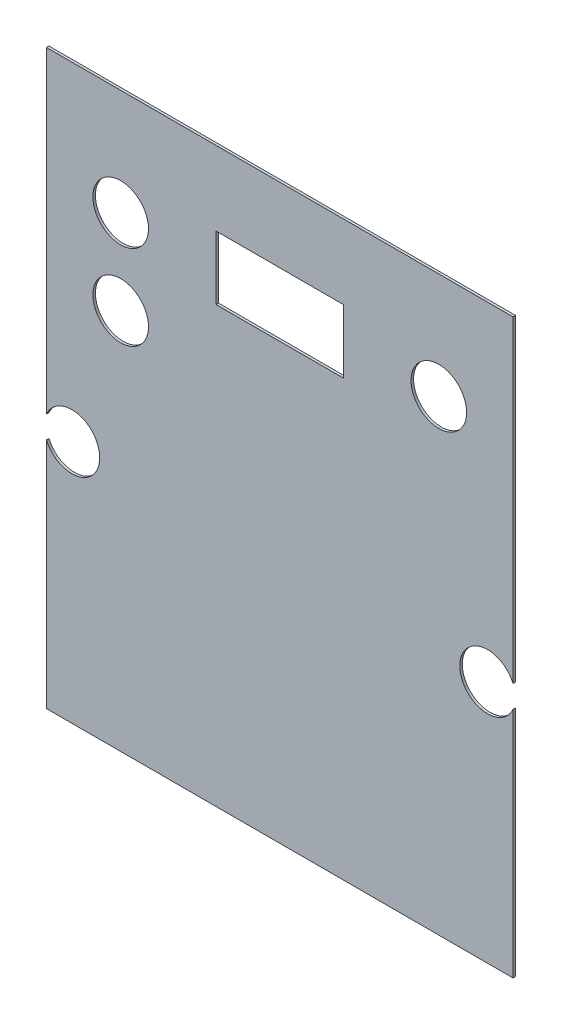
SolidWorks part; units mm, degrees
ref_plane "Front" through (0, 0, 0) normal (0, 0, 1) x (1, 0, 0)
ref_plane "Top" through (0, 0, 0) normal (0, 1, 0) x (1, 0, 0)
ref_plane "Right" through (0, 0, 0) normal (1, 0, 0) x (0, 0, -1)
sketch "Model" plane through (0, 0, 0) normal (0, 0, 1) x (1, 0, 0)
  line L0 (0.0762, 0) -> (0.0762, 34.29)
  line L1 (-0.0762, 34.29) -> (-0.0762, 0)
  line L2 (0, 34.2138) -> (27.94, 34.2138)
  line L3 (27.94, 34.3662) -> (0, 34.3662)
  line L4 (27.8638, 34.29) -> (27.8638, 0)
  line L5 (28.0162, 0) -> (28.0162, 34.29)
  line L6 (27.94, 0.0762) -> (0, 0.0762)
  line L7 (0, -0.0762) -> (27.94, -0.0762)
  line L8 (15.1638, 21.336) -> (15.1638, 19.1135)
  line L9 (15.3162, 19.1135) -> (15.3162, 21.336)
  line L10 (15.24, 19.0373) -> (18.6055, 19.0373)
  line L11 (18.6055, 19.1897) -> (15.24, 19.1897)
  line L12 (18.6817, 19.1135) -> (18.6817, 21.3995)
  line L13 (18.5293, 21.3995) -> (18.5293, 19.1135)
  line L14 (18.6055, 21.4757) -> (15.24, 21.4757)
  line L15 (15.24, 21.3233) -> (18.6055, 21.3233)
  line L16 (1.9255, 9.8453) -> (1.4521, 10.1036)
  line L17 (1.3913, 9.9921) -> (1.8647, 9.7338)
  line L18 (20.9755, 9.7183) -> (20.5021, 9.9766)
  line L19 (20.4413, 9.8651) -> (20.9147, 9.6068)
  line L20 (3.8735, 9.0805) -> (4.39, 9.0805)
  line L21 (4.39, 9.2075) -> (3.8735, 9.2075)
  line L22 (4.7978, 9.4883) -> (4.7978, 9.6605)
  line L23 (4.6708, 9.6605) -> (4.6708, 9.4883)
  line L24 (4.39, 10.0683) -> (3.8735, 10.0683)
  line L25 (3.8735, 9.9413) -> (4.39, 9.9413)
  line L26 (3.937, 10.0048) -> (3.937, 10.6934)
  line L27 (3.81, 10.6934) -> (3.81, 10.0048)
  line L28 (3.8735, 10.6299) -> (4.7343, 10.6299)
  line L29 (4.7343, 10.7569) -> (3.8735, 10.7569)
  line L30 (22.987, 8.9535) -> (23.5035, 8.9535)
  line L31 (23.5035, 9.0805) -> (22.987, 9.0805)
  line L32 (23.9113, 9.3613) -> (23.9113, 9.5335)
  line L33 (23.7843, 9.5335) -> (23.7843, 9.3613)
  line L34 (23.5035, 9.9413) -> (22.987, 9.9413)
  line L35 (22.987, 9.8143) -> (23.5035, 9.8143)
  line L36 (23.0505, 9.8778) -> (23.0505, 10.5664)
  line L37 (22.9235, 10.5664) -> (22.9235, 9.8778)
  line L38 (22.987, 10.5029) -> (23.8478, 10.5029)
  line L39 (23.8478, 10.6299) -> (22.987, 10.6299)
  line L40 (6.635, 9.9413) -> (6.8933, 9.9413)
  line L41 (6.8933, 10.0683) -> (6.635, 10.0683)
  line L42 (6.8298, 10.0048) -> (6.8298, 9.144)
  line L43 (6.9568, 9.144) -> (6.9568, 10.0048)
  line L44 (6.8933, 9.2075) -> (6.3768, 9.2075)
  line L45 (6.3768, 9.0805) -> (6.8933, 9.0805)
  line L46 (6.096, 9.4883) -> (6.096, 10.3491)
  line L47 (5.969, 10.3491) -> (5.969, 9.4883)
  line L48 (6.3768, 10.6299) -> (6.8933, 10.6299)
  line L49 (6.8933, 10.7569) -> (6.3768, 10.7569)
  line L50 (17.4935, 9.7508) -> (17.7518, 9.7508)
  line L51 (17.7518, 9.8778) -> (17.4935, 9.8778)
  line L52 (17.6883, 9.8143) -> (17.6883, 8.9535)
  line L53 (17.8153, 8.9535) -> (17.8153, 9.8143)
  line L54 (17.7518, 9.017) -> (17.2353, 9.017)
  line L55 (17.2353, 8.89) -> (17.7518, 8.89)
  line L56 (16.9545, 9.2978) -> (16.9545, 10.1586)
  line L57 (16.8275, 10.1586) -> (16.8275, 9.2978)
  line L58 (17.2353, 10.4394) -> (17.7518, 10.4394)
  line L59 (17.7518, 10.5664) -> (17.2353, 10.5664)
  line L60 (25.7485, 9.8143) -> (26.0068, 9.8143)
  line L61 (26.0068, 9.9413) -> (25.7485, 9.9413)
  line L62 (25.9433, 9.8778) -> (25.9433, 9.017)
  line L63 (26.0703, 9.017) -> (26.0703, 9.8778)
  line L64 (26.0068, 9.0805) -> (25.4903, 9.0805)
  line L65 (25.4903, 8.9535) -> (26.0068, 8.9535)
  line L66 (25.2095, 9.3613) -> (25.2095, 10.2221)
  line L67 (25.0825, 10.2221) -> (25.0825, 9.3613)
  line L68 (25.4903, 10.5029) -> (26.0068, 10.5029)
  line L69 (26.0068, 10.6299) -> (25.4903, 10.6299)
  line L70 (8.413, 14.0053) -> (8.6713, 14.0053)
  line L71 (8.6713, 14.1323) -> (8.413, 14.1323)
  line L72 (8.6078, 14.0688) -> (8.6078, 13.208)
  line L73 (8.7348, 13.208) -> (8.7348, 14.0688)
  line L74 (8.6713, 13.2715) -> (8.1548, 13.2715)
  line L75 (8.1548, 13.1445) -> (8.6713, 13.1445)
  line L76 (7.874, 13.5523) -> (7.874, 14.4131)
  line L77 (7.747, 14.4131) -> (7.747, 13.5523)
  line L78 (8.1548, 14.6939) -> (8.6713, 14.6939)
  line L79 (8.6713, 14.8209) -> (8.1548, 14.8209)
  line L80 (6.5405, 15.6845) -> (6.9709, 15.6845)
  line L81 (6.9709, 15.8115) -> (6.5405, 15.8115)
  line L82 (6.5405, 17.2339) -> (7.057, 17.2339)
  line L83 (7.057, 17.3609) -> (6.5405, 17.3609)
  line L84 (7.057, 16.6723) -> (6.7127, 16.6723)
  line L85 (6.7127, 16.5453) -> (7.057, 16.5453)
  line L86 (8.032, 15.748) -> (8.032, 15.8341)
  line L87 (7.905, 15.8341) -> (7.905, 15.748)
  line L88 (7.9685, 15.7706) -> (8.0545, 15.7706)
  line L89 (8.0545, 15.8976) -> (7.9685, 15.8976)
  line L90 (7.991, 15.8341) -> (7.991, 15.748)
  line L91 (8.118, 15.748) -> (8.118, 15.8341)
  line L92 (8.0545, 15.8115) -> (7.9685, 15.8115)
  line L93 (7.9685, 15.6845) -> (8.0545, 15.6845)
  line L94 (8.6217, 15.6845) -> (9.0521, 15.6845)
  line L95 (9.0521, 15.8115) -> (8.6217, 15.8115)
  line L96 (8.6217, 17.2339) -> (9.1382, 17.2339)
  line L97 (9.1382, 17.3609) -> (8.6217, 17.3609)
  line L98 (9.1382, 16.6723) -> (8.7939, 16.6723)
  line L99 (8.7939, 16.5453) -> (9.1382, 16.5453)
  line L100 (14.5382, 8.8064) -> (15.0547, 10.3558)
  line L101 (14.9342, 10.396) -> (14.4178, 8.8466)
  line L102 (14.9342, 10.3558) -> (15.4507, 8.8064)
  line L103 (15.5712, 8.8466) -> (15.0547, 10.396)
  line L104 (15.3818, 9.2774) -> (14.6071, 9.2774)
  line L105 (14.6071, 9.1503) -> (15.3818, 9.1503)
  line L106 (9.5885, 9.7508) -> (10.0189, 9.7508)
  line L107 (10.0189, 9.8778) -> (9.5885, 9.8778)
  line L108 (10.0189, 9.017) -> (9.5885, 9.017)
  line L109 (9.5885, 8.89) -> (10.0189, 8.89)
  line L110 (9.652, 8.9535) -> (9.652, 10.5029)
  line L111 (9.525, 10.5029) -> (9.525, 8.9535)
  line L112 (9.5885, 10.4394) -> (10.0189, 10.4394)
  line L113 (10.0189, 10.5664) -> (9.5885, 10.5664)
  line L114 (12.065, 9.429) -> (13.0979, 9.429)
  line L115 (13.0979, 9.556) -> (12.065, 9.556)
  line L116 (12.645, 8.9761) -> (12.645, 10.009)
  line L117 (12.518, 10.009) -> (12.518, 8.9761)
  line L118 (6.6642, 18.4584) -> (7.1807, 20.0078)
  line L119 (7.0602, 20.048) -> (6.5438, 18.4986)
  line L120 (7.0602, 20.0078) -> (7.5767, 18.4584)
  line L121 (7.6972, 18.4986) -> (7.1807, 20.048)
  line L122 (7.5078, 18.9293) -> (6.7331, 18.9293)
  line L123 (6.7331, 18.8024) -> (7.5078, 18.8024)
  line L124 (8.2767, 18.4785) -> (8.2767, 19.5114)
  line L125 (8.1497, 19.5114) -> (8.1497, 18.4785)
  line L126 (8.2132, 19.4479) -> (8.6436, 19.4479)
  line L127 (8.6436, 19.5749) -> (8.2132, 19.5749)
  line L128 (8.8383, 19.2532) -> (8.8383, 18.4785)
  line L129 (8.9653, 18.4785) -> (8.9653, 19.2532)
  line L130 (18.6507, 23.9649) -> (18.6507, 22.4155)
  line L131 (18.7777, 22.4155) -> (18.7777, 23.9649)
  line L132 (18.542, 22.352) -> (18.8863, 22.352)
  line L133 (18.8863, 22.479) -> (18.542, 22.479)
  line L134 (18.542, 23.9014) -> (18.8863, 23.9014)
  line L135 (18.8863, 24.0284) -> (18.542, 24.0284)
  line L136 (19.5731, 22.4155) -> (19.5731, 23.4484)
  line L137 (19.4461, 23.4484) -> (19.4461, 22.4155)
  line L138 (19.5096, 23.3849) -> (19.9399, 23.3849)
  line L139 (19.9399, 23.5119) -> (19.5096, 23.5119)
  line L140 (20.1347, 23.1902) -> (20.1347, 22.4155)
  line L141 (20.2617, 22.4155) -> (20.2617, 23.1902)
  line L142 (21.4657, 23.9649) -> (21.4657, 22.4155)
  line L143 (21.5927, 22.4155) -> (21.5927, 23.9649)
  line L144 (21.5292, 22.479) -> (21.0989, 22.479)
  line L145 (21.0989, 22.352) -> (21.5292, 22.352)
  line L146 (20.9041, 22.6737) -> (20.9041, 23.1902)
  line L147 (20.7771, 23.1902) -> (20.7771, 22.6737)
  line L148 (21.0989, 23.3849) -> (21.5292, 23.3849)
  line L149 (21.5292, 23.5119) -> (21.0989, 23.5119)
  line L150 (22.1887, 22.3803) -> (22.8773, 23.4132)
  line L151 (22.7716, 23.4836) -> (22.083, 22.4507)
  line L152 (22.083, 23.4132) -> (22.7716, 22.3803)
  line L153 (22.8773, 22.4507) -> (22.1887, 23.4836)
  line L154 (13.6525, 19.177) -> (14.169, 19.177)
  line L155 (14.169, 19.304) -> (13.6525, 19.304)
  line L156 (14.5768, 19.5848) -> (14.5768, 19.757)
  line L157 (14.4498, 19.757) -> (14.4498, 19.5848)
  line L158 (14.169, 20.1648) -> (13.6525, 20.1648)
  line L159 (13.6525, 20.0378) -> (14.169, 20.0378)
  line L160 (13.716, 20.1013) -> (13.716, 20.7899)
  line L161 (13.589, 20.7899) -> (13.589, 20.1013)
  line L162 (13.6525, 20.7264) -> (14.5133, 20.7264)
  line L163 (14.5133, 20.8534) -> (13.6525, 20.8534)
  line L164 (18.9865, 19.177) -> (19.4169, 19.177)
  line L165 (19.4169, 19.304) -> (18.9865, 19.304)
  line L166 (18.9865, 20.7264) -> (19.503, 20.7264)
  line L167 (19.503, 20.8534) -> (18.9865, 20.8534)
  line L168 (19.503, 20.1648) -> (19.1587, 20.1648)
  line L169 (19.1587, 20.0378) -> (19.503, 20.0378)
  line L170 (20.478, 19.2405) -> (20.478, 19.3266)
  line L171 (20.351, 19.3266) -> (20.351, 19.2405)
  line L172 (20.4145, 19.2631) -> (20.5005, 19.2631)
  line L173 (20.5005, 19.3901) -> (20.4145, 19.3901)
  line L174 (20.437, 19.3266) -> (20.437, 19.2405)
  line L175 (20.564, 19.2405) -> (20.564, 19.3266)
  line L176 (20.5005, 19.304) -> (20.4145, 19.304)
  line L177 (20.4145, 19.177) -> (20.5005, 19.177)
  line L178 (21.0677, 19.177) -> (21.4981, 19.177)
  line L179 (21.4981, 19.304) -> (21.0677, 19.304)
  line L180 (21.0677, 20.7264) -> (21.5842, 20.7264)
  line L181 (21.5842, 20.8534) -> (21.0677, 20.8534)
  line L182 (21.5842, 20.1648) -> (21.2399, 20.1648)
  line L183 (21.2399, 20.0378) -> (21.5842, 20.0378)
  line L184 (20.8915, 2.794) -> (20.8915, 4.3434)
  line L185 (20.7645, 4.3434) -> (20.7645, 2.794)
  line L186 (20.828, 4.2799) -> (21.5166, 4.2799)
  line L187 (21.5166, 4.4069) -> (20.828, 4.4069)
  line L188 (20.828, 3.5913) -> (21.5166, 3.5913)
  line L189 (21.5166, 3.7183) -> (20.828, 3.7183)
  line L190 (21.9421, 4.3296) -> (22.2864, 2.7802)
  line L191 (22.4104, 2.8078) -> (22.066, 4.3572)
  line L192 (22.4086, 2.7739) -> (22.7529, 3.8069)
  line L193 (22.6324, 3.847) -> (22.2881, 2.8141)
  line L194 (22.6324, 3.8069) -> (22.9768, 2.7739)
  line L195 (23.0972, 2.8141) -> (22.7529, 3.847)
  line L196 (23.099, 2.7802) -> (23.4433, 4.3296)
  line L197 (23.3193, 4.3572) -> (22.975, 2.8078)
  line L198 (24.0602, 2.794) -> (24.0602, 4.3434)
  line L199 (23.9332, 4.3434) -> (23.9332, 2.794)
  line L200 (23.9966, 4.2799) -> (24.427, 4.2799)
  line L201 (24.427, 4.4069) -> (23.9966, 4.4069)
  line L202 (24.7939, 3.913) -> (24.7939, 3.2244)
  line L203 (24.9209, 3.2244) -> (24.9209, 3.913)
  line L204 (24.427, 2.8575) -> (23.9966, 2.8575)
  line L205 (23.9966, 2.7305) -> (24.427, 2.7305)
  line L206 (2.2225, 2.921) -> (2.2225, 4.4704)
  line L207 (2.0955, 4.4704) -> (2.0955, 2.921)
  line L208 (2.159, 4.4069) -> (2.5894, 4.4069)
  line L209 (2.5894, 4.5339) -> (2.159, 4.5339)
  line L210 (2.5894, 3.6731) -> (2.159, 3.6731)
  line L211 (2.159, 3.5461) -> (2.5894, 3.5461)
  line L212 (3.0766, 2.9494) -> (2.7323, 3.638)
  line L213 (2.6187, 3.5812) -> (2.963, 2.8926)
  line L214 (4.3779, 2.9845) -> (3.6893, 2.9845)
  line L215 (3.6893, 2.8575) -> (4.3779, 2.8575)
  line L216 (3.7528, 2.921) -> (3.7528, 4.4704)
  line L217 (3.6258, 4.4704) -> (3.6258, 2.921)
  line L218 (3.6893, 4.4069) -> (4.3779, 4.4069)
  line L219 (4.3779, 4.5339) -> (3.6893, 4.5339)
  line L220 (3.6893, 3.7183) -> (4.2058, 3.7183)
  line L221 (4.2058, 3.8453) -> (3.6893, 3.8453)
  line L222 (4.7791, 4.4503) -> (5.2955, 2.9009)
  line L223 (5.416, 2.9411) -> (4.8996, 4.4905)
  line L224 (5.416, 2.9009) -> (5.9325, 4.4503)
  line L225 (5.812, 4.4905) -> (5.2955, 2.9411)
  line L226 (10.8486, 2.9845) -> (10.16, 2.9845)
  line L227 (10.16, 2.8575) -> (10.8486, 2.8575)
  line L228 (10.2235, 2.921) -> (10.2235, 4.4704)
  line L229 (10.0965, 4.4704) -> (10.0965, 2.921)
  line L230 (10.16, 4.4069) -> (10.8486, 4.4069)
  line L231 (10.8486, 4.5339) -> (10.16, 4.5339)
  line L232 (10.16, 3.7183) -> (10.6765, 3.7183)
  line L233 (10.6765, 3.8453) -> (10.16, 3.8453)
  line L234 (11.4961, 2.921) -> (11.4961, 3.9539)
  line L235 (11.3691, 3.9539) -> (11.3691, 2.921)
  line L236 (11.4326, 3.8904) -> (11.863, 3.8904)
  line L237 (11.863, 4.0174) -> (11.4326, 4.0174)
  line L238 (12.0577, 3.6957) -> (12.0577, 2.921)
  line L239 (12.1847, 2.921) -> (12.1847, 3.6957)
  line L240 (13.3747, 2.9845) -> (13.0304, 2.9845)
  line L241 (13.0304, 2.8575) -> (13.3747, 2.8575)
  line L242 (12.8356, 3.1792) -> (12.8356, 3.6957)
  line L243 (12.7086, 3.6957) -> (12.7086, 3.1792)
  line L244 (13.0304, 3.8904) -> (13.3747, 3.8904)
  line L245 (13.3747, 4.0174) -> (13.0304, 4.0174)
  line L246 (13.9737, 3.2653) -> (13.9737, 3.6096)
  line L247 (13.8467, 3.6096) -> (13.8467, 3.2653)
  line L248 (14.5354, 3.6096) -> (14.5354, 3.2653)
  line L249 (14.6624, 3.2653) -> (14.6624, 3.6096)
  line L250 (15.8169, 4.4704) -> (15.8169, 2.921)
  line L251 (15.9439, 2.921) -> (15.9439, 4.4704)
  line L252 (15.8804, 2.9845) -> (15.45, 2.9845)
  line L253 (15.45, 2.8575) -> (15.8804, 2.8575)
  line L254 (15.2553, 3.1792) -> (15.2553, 3.6957)
  line L255 (15.1283, 3.6957) -> (15.1283, 3.1792)
  line L256 (15.45, 3.8904) -> (15.8804, 3.8904)
  line L257 (15.8804, 4.0174) -> (15.45, 4.0174)
  line L258 (17.2252, 2.9845) -> (16.7948, 2.9845)
  line L259 (16.7948, 2.8575) -> (17.2252, 2.8575)
  line L260 (16.6, 3.1792) -> (16.6, 3.6096)
  line L261 (16.473, 3.6096) -> (16.473, 3.1792)
  line L262 (17.1617, 3.6096) -> (17.1617, 3.4375)
  line L263 (17.2887, 3.4375) -> (17.2887, 3.6096)
  line L264 (17.2252, 3.501) -> (16.5365, 3.501)
  line L265 (16.5365, 3.374) -> (17.2252, 3.374)
  line L266 (17.9458, 2.921) -> (17.9458, 3.9539)
  line L267 (17.8188, 3.9539) -> (17.8188, 2.921)
  line L268 (17.8823, 3.8904) -> (18.3988, 3.8904)
  line L269 (18.3988, 4.0174) -> (17.8823, 4.0174)
  line L270 (18.3353, 3.9539) -> (18.3353, 3.7818)
  line L271 (18.4623, 3.7818) -> (18.4623, 3.9539)
  line L272 (6.1454, 30.9245) -> (6.1454, 32.4739)
  line L273 (6.0184, 32.4739) -> (6.0184, 30.9245)
  line L274 (5.6515, 32.4104) -> (6.5123, 32.4104)
  line L275 (6.5123, 32.5374) -> (5.6515, 32.5374)
  line L276 (7.0131, 30.9044) -> (7.5296, 32.4538)
  line L277 (7.4091, 32.494) -> (6.8926, 30.9446)
  line L278 (7.4091, 32.4538) -> (7.9256, 30.9044)
  line L279 (8.0461, 30.9446) -> (7.5296, 32.494)
  line L280 (7.8567, 31.3753) -> (7.082, 31.3753)
  line L281 (7.082, 31.2484) -> (7.8567, 31.2484)
  line L282 (8.5143, 32.4739) -> (8.5143, 30.9245)
  line L283 (8.6413, 30.9245) -> (8.6413, 32.4739)
  line L284 (8.5778, 30.861) -> (9.2665, 30.861)
  line L285 (9.2665, 30.988) -> (8.5778, 30.988)
  line L286 (9.8774, 31.3549) -> (9.8774, 32.0435)
  line L287 (9.7504, 32.0435) -> (9.7504, 31.3549)
  line L288 (10.6112, 32.0435) -> (10.6112, 31.3549)
  line L289 (10.7382, 31.3549) -> (10.7382, 32.0435)
  line L290 (11.4135, 30.9245) -> (11.4135, 32.4739)
  line L291 (11.2865, 32.4739) -> (11.2865, 30.9245)
  line L292 (11.2945, 32.4431) -> (12.1553, 30.8937)
  line L293 (12.2663, 30.9553) -> (11.4056, 32.5047)
  line L294 (12.2743, 30.9245) -> (12.2743, 32.4739)
  line L295 (12.1473, 32.4739) -> (12.1473, 30.9245)
  line L296 (13.7483, 31.7218) -> (14.1787, 31.7218)
  line L297 (14.1787, 31.8488) -> (13.7483, 31.8488)
  line L298 (14.1787, 30.988) -> (13.7483, 30.988)
  line L299 (13.7483, 30.861) -> (14.1787, 30.861)
  line L300 (13.8118, 30.9245) -> (13.8118, 32.4739)
  line L301 (13.6848, 32.4739) -> (13.6848, 30.9245)
  line L302 (13.7483, 32.4104) -> (14.1787, 32.4104)
  line L303 (14.1787, 32.5374) -> (13.7483, 32.5374)
  line L304 (15.2735, 30.9245) -> (15.2735, 31.9574)
  line L305 (15.1465, 31.9574) -> (15.1465, 30.9245)
  line L306 (15.21, 31.8939) -> (15.7264, 31.8939)
  line L307 (15.7264, 32.0209) -> (15.21, 32.0209)
  line L308 (15.6629, 31.9574) -> (15.6629, 31.7853)
  line L309 (15.7899, 31.7853) -> (15.7899, 31.9574)
  line L310 (16.8818, 30.988) -> (16.4514, 30.988)
  line L311 (16.4514, 30.861) -> (16.8818, 30.861)
  line L312 (16.2567, 31.1827) -> (16.2567, 31.6131)
  line L313 (16.1297, 31.6131) -> (16.1297, 31.1827)
  line L314 (16.8183, 31.6131) -> (16.8183, 31.441)
  line L315 (16.9453, 31.441) -> (16.9453, 31.6131)
  line L316 (16.8818, 31.5045) -> (16.1932, 31.5045)
  line L317 (16.1932, 31.3775) -> (16.8818, 31.3775)
  line L318 (18.1633, 31.5905) -> (17.776, 31.5905)
  line L319 (17.776, 31.4635) -> (18.1633, 31.4635)
  line L320 (17.776, 30.861) -> (18.1633, 30.861)
  line L321 (18.1633, 30.988) -> (17.776, 30.988)
  line L322 (18.2268, 30.9245) -> (18.2268, 31.6992)
  line L323 (18.0998, 31.6992) -> (18.0998, 30.9245)
  line L324 (17.9051, 32.0209) -> (17.5608, 32.0209)
  line L325 (17.5608, 31.8939) -> (17.9051, 31.8939)
  line L326 (18.9483, 30.9245) -> (18.9483, 32.4739)
  line L327 (18.8213, 32.4739) -> (18.8213, 30.9245)
  line L328 (19.5353, 32.0082) -> (18.8467, 31.4918)
  line L329 (18.9229, 31.3902) -> (19.6115, 31.9066)
  line L330 (19.6295, 30.9542) -> (19.2422, 31.6859)
  line L331 (19.1299, 31.6265) -> (19.5173, 30.8948)
  line L332 (20.1713, 31.2688) -> (20.1713, 31.6131)
  line L333 (20.0443, 31.6131) -> (20.0443, 31.2688)
  line L334 (20.733, 31.6131) -> (20.733, 31.2688)
  line L335 (20.86, 31.2688) -> (20.86, 31.6131)
  line L336 (21.3823, 31.9574) -> (21.3823, 31.1827)
  line L337 (21.5093, 31.1827) -> (21.5093, 31.9574)
  line L338 (21.704, 30.861) -> (22.1344, 30.861)
  line L339 (22.1344, 30.988) -> (21.704, 30.988)
  line L340 (22.1979, 30.9245) -> (22.1979, 31.9574)
  line L341 (22.0709, 31.9574) -> (22.0709, 30.9245)
  line L342 (22.6607, 31.8939) -> (23.1772, 31.8939)
  line L343 (23.1772, 32.0209) -> (22.6607, 32.0209)
  line L344 (22.7694, 32.4739) -> (22.7694, 31.1827)
  line L345 (22.8964, 31.1827) -> (22.8964, 32.4739)
  line L346 (23.0911, 30.861) -> (23.1772, 30.861)
  line L347 (23.1772, 30.988) -> (23.0911, 30.988)
  line L348 (7.9911, 28.194) -> (7.3025, 28.194)
  line L349 (7.3025, 28.067) -> (7.9911, 28.067)
  line L350 (7.366, 28.1305) -> (7.366, 29.6799)
  line L351 (7.239, 29.6799) -> (7.239, 28.1305)
  line L352 (7.3025, 29.6164) -> (7.9911, 29.6164)
  line L353 (7.9911, 29.7434) -> (7.3025, 29.7434)
  line L354 (7.3025, 28.9278) -> (7.819, 28.9278)
  line L355 (7.819, 29.0548) -> (7.3025, 29.0548)
  line L356 (8.6713, 28.1305) -> (8.6713, 29.6799)
  line L357 (8.5443, 29.6799) -> (8.5443, 28.1305)
  line L358 (8.6078, 29.6164) -> (9.0382, 29.6164)
  line L359 (9.0382, 29.7434) -> (8.6078, 29.7434)
  line L360 (9.0382, 28.8826) -> (8.6078, 28.8826)
  line L361 (8.6078, 28.7556) -> (9.0382, 28.7556)
  line L362 (10.0947, 29.6799) -> (10.0947, 28.1305)
  line L363 (10.2217, 28.1305) -> (10.2217, 29.6799)
  line L364 (9.9861, 28.067) -> (10.3304, 28.067)
  line L365 (10.3304, 28.194) -> (9.9861, 28.194)
  line L366 (9.9861, 29.6164) -> (10.3304, 29.6164)
  line L367 (10.3304, 29.7434) -> (9.9861, 29.7434)
  line L368 (11.602, 28.194) -> (11.2577, 28.194)
  line L369 (11.2577, 28.067) -> (11.602, 28.067)
  line L370 (10.9769, 28.4748) -> (10.9769, 29.3356)
  line L371 (10.8499, 29.3356) -> (10.8499, 28.4748)
  line L372 (11.2577, 29.6164) -> (11.602, 29.6164)
  line L373 (11.602, 29.7434) -> (11.2577, 29.7434)
  line L374 (13.0704, 28.1305) -> (13.0704, 29.6799)
  line L375 (12.9434, 29.6799) -> (12.9434, 28.1305)
  line L376 (13.0069, 29.6164) -> (13.4373, 29.6164)
  line L377 (13.4373, 29.7434) -> (13.0069, 29.7434)
  line L378 (13.4373, 28.8826) -> (13.0069, 28.8826)
  line L379 (13.0069, 28.7556) -> (13.4373, 28.7556)
  line L380 (13.9245, 28.1589) -> (13.5801, 28.8475)
  line L381 (13.4665, 28.7907) -> (13.8109, 28.1021)
  line L382 (14.5354, 28.4748) -> (14.5354, 28.8191)
  line L383 (14.4084, 28.8191) -> (14.4084, 28.4748)
  line L384 (15.097, 28.8191) -> (15.097, 28.4748)
  line L385 (15.224, 28.4748) -> (15.224, 28.8191)
  line L386 (15.7531, 29.6799) -> (15.7531, 28.1305)
  line L387 (15.8801, 28.1305) -> (15.8801, 29.6799)
  line L388 (15.8166, 28.067) -> (16.247, 28.067)
  line L389 (16.247, 28.194) -> (15.8166, 28.194)
  line L390 (16.5688, 28.3887) -> (16.5688, 28.9052)
  line L391 (16.4418, 28.9052) -> (16.4418, 28.3887)
  line L392 (16.247, 29.2269) -> (15.8166, 29.2269)
  line L393 (15.8166, 29.0999) -> (16.247, 29.0999)
  line L394 (17.1617, 28.4748) -> (17.1617, 28.8191)
  line L395 (17.0347, 28.8191) -> (17.0347, 28.4748)
  line L396 (17.7233, 28.8191) -> (17.7233, 28.4748)
  line L397 (17.8503, 28.4748) -> (17.8503, 28.8191)
  line L398 (18.2636, 29.0999) -> (18.78, 29.0999)
  line L399 (18.78, 29.2269) -> (18.2636, 29.2269)
  line L400 (18.3723, 29.6799) -> (18.3723, 28.3887)
  line L401 (18.4993, 28.3887) -> (18.4993, 29.6799)
  line L402 (18.694, 28.067) -> (18.78, 28.067)
  line L403 (18.78, 28.194) -> (18.694, 28.194)
  line L404 (19.2785, 29.0999) -> (19.9671, 29.0999)
  line L405 (19.9671, 29.2269) -> (19.2785, 29.2269)
  line L406 (19.9143, 29.1986) -> (19.2256, 28.1657)
  line L407 (19.3313, 28.0953) -> (20.0199, 29.1282)
  line L408 (19.2785, 28.067) -> (19.9671, 28.067)
  line L409 (19.9671, 28.194) -> (19.2785, 28.194)
  line L410 (7.493, 25.2095) -> (7.493, 26.7589)
  line L411 (7.366, 26.7589) -> (7.366, 25.2095)
  line L412 (7.4295, 26.6954) -> (8.1181, 26.6954)
  line L413 (8.1181, 26.8224) -> (7.4295, 26.8224)
  line L414 (7.4295, 26.0068) -> (8.1181, 26.0068)
  line L415 (8.1181, 26.1338) -> (7.4295, 26.1338)
  line L416 (9.3343, 25.8755) -> (8.947, 25.8755)
  line L417 (8.947, 25.7485) -> (9.3343, 25.7485)
  line L418 (8.947, 25.146) -> (9.3343, 25.146)
  line L419 (9.3343, 25.273) -> (8.947, 25.273)
  line L420 (9.3978, 25.2095) -> (9.3978, 25.9842)
  line L421 (9.2708, 25.9842) -> (9.2708, 25.2095)
  line L422 (9.0761, 26.3059) -> (8.7318, 26.3059)
  line L423 (8.7318, 26.1789) -> (9.0761, 26.1789)
  line L424 (9.9499, 26.7589) -> (9.9499, 25.4677)
  line L425 (10.0769, 25.4677) -> (10.0769, 26.7589)
  line L426 (10.7427, 26.7589) -> (10.7427, 25.4677)
  line L427 (10.8697, 25.4677) -> (10.8697, 26.7589)
  line L428 (13.0653, 26.1114) -> (12.3337, 25.2506)
  line L429 (12.4304, 25.1684) -> (13.1621, 26.0292)
  line L430 (12.382, 25.146) -> (13.2428, 25.146)
  line L431 (13.2428, 25.273) -> (12.382, 25.273)
  line L432 (14.0043, 25.5141) -> (14.6929, 26.3749)
  line L433 (14.5937, 26.4543) -> (13.9051, 25.5935)
  line L434 (15.3949, 26.365) -> (15.8252, 26.7093)
  line L435 (15.7459, 26.8085) -> (15.3155, 26.4642)
  line L436 (15.7221, 26.7589) -> (15.7221, 25.2095)
  line L437 (15.8491, 25.2095) -> (15.8491, 26.7589)
  line L438 (15.3552, 25.146) -> (16.216, 25.146)
  line L439 (16.216, 25.273) -> (15.3552, 25.273)
  line L440 (19.1342, 25.7485) -> (20.1671, 25.7485)
  line L441 (20.1671, 25.8755) -> (19.1342, 25.8755)
  line L442 (21.476, 26.2224) -> (21.8203, 25.1894)
  line L443 (21.9408, 25.2296) -> (21.5965, 26.2625)
  line L444 (21.9408, 25.1894) -> (22.2851, 26.2224)
  line L445 (22.1646, 26.2625) -> (21.8203, 25.2296)
  line L446 (23.4714, 26.1114) -> (22.7397, 25.2506)
  line L447 (22.8365, 25.1684) -> (23.5681, 26.0292)
  line L448 (22.7881, 25.146) -> (23.6488, 25.146)
  line L449 (23.6488, 25.273) -> (22.7881, 25.273)
  line L450 (15.9639, 20.32) -> (16.002, 20.32)
  circle A0 centre (17.018, 23.114) radius 0.8382
  circle A1 centre (17.018, 23.114) radius 0.8382
  circle A2 centre (11.049, 19.05) radius 0.8382
  circle A3 centre (11.049, 19.05) radius 0.8382
  circle A4 centre (11.049, 16.51) radius 0.8382
  circle A5 centre (11.049, 16.51) radius 0.8382
  circle A6 centre (11.049, 13.97) radius 0.8382
  circle A7 centre (11.049, 13.97) radius 0.8382
  circle A8 centre (20.955, 7.62) radius 0.8382
  circle A9 centre (20.955, 7.62) radius 0.8382
  circle A10 centre (23.495, 7.62) radius 0.8382
  circle A11 centre (23.495, 7.62) radius 0.8382
  circle A12 centre (26.035, 7.62) radius 0.8382
  circle A13 centre (26.035, 7.62) radius 0.8382
  circle A14 centre (1.905, 7.62) radius 0.8382
  circle A15 centre (1.905, 7.62) radius 0.8382
  circle A16 centre (4.445, 7.62) radius 0.8382
  circle A17 centre (4.445, 7.62) radius 0.8382
  circle A18 centre (6.985, 7.62) radius 0.8382
  circle A19 centre (6.985, 7.62) radius 0.8382
  circle A20 centre (10.16, 7.62) radius 0.8382
  circle A21 centre (10.16, 7.62) radius 0.8382
  circle A22 centre (12.7, 7.62) radius 0.8382
  circle A23 centre (12.7, 7.62) radius 0.8382
  circle A24 centre (15.24, 7.62) radius 0.8382
  circle A25 centre (15.24, 7.62) radius 0.8382
  circle A26 centre (17.78, 7.62) radius 0.8382
  circle A27 centre (17.78, 7.62) radius 0.8382
  circle A28 centre (11.049, 22.86) radius 0.4032
  circle A29 centre (11.049, 22.86) radius 0.4032
  circle A30 centre (11.049, 21.082) radius 0.4032
  circle A31 centre (11.049, 21.082) radius 0.4032
  circle A32 centre (4.445, 12.7) radius 0.4032
  circle A33 centre (4.445, 12.7) radius 0.4032
  circle A34 centre (23.495, 16.51) radius 0.4032
  circle A35 centre (23.495, 16.51) radius 0.4032
  circle A36 centre (23.495, 21.59) radius 0.4032
  circle A37 centre (23.495, 21.59) radius 0.4032
  circle A38 centre (17.145, 16.5735) radius 0.4032
  circle A39 centre (17.145, 16.5735) radius 0.4032
  circle A40 centre (17.145, 13.97) radius 0.4032
  circle A41 centre (17.145, 13.97) radius 0.4032
  circle A42 centre (4.445, 17.78) radius 0.4032
  circle A43 centre (4.445, 17.78) radius 0.4032
  circle A44 centre (4.445, 15.24) radius 0.4032
  circle A45 centre (4.445, 15.24) radius 0.4032
  circle A46 centre (4.445, 27.94) radius 1.5113
  circle A47 centre (4.445, 27.94) radius 1.6637
  circle A48 centre (23.495, 27.94) radius 1.5113
  circle A49 centre (23.495, 27.94) radius 1.6637
  circle A50 centre (1.524, 14.605) radius 1.5113
  circle A51 centre (1.524, 14.605) radius 1.6637
  circle A52 centre (26.416, 14.605) radius 1.5113
  circle A53 centre (26.416, 14.605) radius 1.6637
  circle A54 centre (4.445, 22.86) radius 1.5113
  circle A55 centre (4.445, 22.86) radius 1.6637
  circle A56 centre (17.018, 23.114) radius 0.5
  circle A57 centre (11.049, 19.05) radius 0.5
  circle A58 centre (11.049, 16.51) radius 0.5
  circle A59 centre (11.049, 13.97) radius 0.5
  circle A60 centre (20.955, 7.62) radius 0.5
  circle A61 centre (23.495, 7.62) radius 0.5
  circle A62 centre (26.035, 7.62) radius 0.5
  circle A63 centre (1.905, 7.62) radius 0.5
  circle A64 centre (4.445, 7.62) radius 0.5
  circle A65 centre (6.985, 7.62) radius 0.5
  circle A66 centre (10.16, 7.62) radius 0.5
  circle A67 centre (12.7, 7.62) radius 0.5
  circle A68 centre (15.24, 7.62) radius 0.5
  circle A69 centre (17.78, 7.62) radius 0.5
  circle A70 centre (11.049, 22.86) radius 0.2
  circle A71 centre (11.049, 21.082) radius 0.2
  circle A72 centre (4.445, 12.7) radius 0.2
  circle A73 centre (23.495, 16.51) radius 0.2
  circle A74 centre (23.495, 21.59) radius 0.2
  circle A75 centre (17.145, 16.5735) radius 0.2
  circle A76 centre (17.145, 13.97) radius 0.2
  circle A77 centre (4.445, 17.78) radius 0.2
  circle A78 centre (4.445, 15.24) radius 0.2
  arc A79 (0.0762, 34.29) -> (-0.0762, 34.29) centre (0, 34.29) ccw
  arc A80 (-0.0762, 0) -> (0.0762, 0) centre (0, 0) ccw
  arc A81 (27.94, 34.2138) -> (27.94, 34.3662) centre (27.94, 34.29) ccw
  arc A82 (0, 34.3662) -> (0, 34.2138) centre (0, 34.29) ccw
  arc A83 (27.8638, 0) -> (28.0162, 0) centre (27.94, 0) ccw
  arc A84 (28.0162, 34.29) -> (27.8638, 34.29) centre (27.94, 34.29) ccw
  arc A85 (0, 0.0762) -> (0, -0.0762) centre (0, 0) ccw
  arc A86 (27.94, -0.0762) -> (27.94, 0.0762) centre (27.94, 0) ccw
  arc A87 (15.1638, 19.1135) -> (15.3162, 19.1135) centre (15.24, 19.1135) ccw
  arc A88 (15.3162, 21.336) -> (15.1638, 21.336) centre (15.24, 21.336) ccw
  arc A89 (18.6055, 19.0373) -> (18.6055, 19.1897) centre (18.6055, 19.1135) ccw
  arc A90 (15.24, 19.1897) -> (15.24, 19.0373) centre (15.24, 19.1135) ccw
  arc A91 (18.6817, 21.3995) -> (18.5293, 21.3995) centre (18.6055, 21.3995) ccw
  arc A92 (18.5293, 19.1135) -> (18.6817, 19.1135) centre (18.6055, 19.1135) ccw
  arc A93 (15.24, 21.4757) -> (15.24, 21.3233) centre (15.24, 21.3995) ccw
  arc A94 (18.6055, 21.3233) -> (18.6055, 21.4757) centre (18.6055, 21.3995) ccw
  arc A95 (1.723, 9.2075) -> (1.723, 9.0805) centre (1.723, 9.144) ccw
  arc A96 (1.723, 9.0805) -> (2.1308, 9.4883) centre (1.723, 9.4883) ccw
  arc A97 (2.1308, 9.4883) -> (2.0038, 9.4883) centre (2.0673, 9.4883) ccw
  arc A98 (1.723, 9.2075) -> (2.0038, 9.4883) centre (1.723, 9.4883) ccw
  arc A99 (1.2516, 9.4039) -> (1.1614, 9.3145) centre (1.2065, 9.3592) ccw
  arc A100 (1.1614, 9.3145) -> (1.723, 9.0805) centre (1.723, 9.8713) ccw
  arc A101 (1.723, 9.0805) -> (1.723, 9.2075) centre (1.723, 9.144) ccw
  arc A102 (1.2516, 9.4039) -> (1.723, 9.2075) centre (1.723, 9.8713) ccw
  arc A103 (1.5938, 10.6299) -> (1.5938, 10.7569) centre (1.5938, 10.6934) ccw
  arc A104 (1.5938, 10.7569) -> (1.186, 10.3491) centre (1.5938, 10.3491) ccw
  arc A105 (1.186, 10.3491) -> (1.313, 10.3491) centre (1.2495, 10.3491) ccw
  arc A106 (1.5938, 10.6299) -> (1.313, 10.3491) centre (1.5938, 10.3491) ccw
  arc A107 (1.9431, 10.5135) -> (2.0193, 10.6151) centre (1.9812, 10.5643) ccw
  arc A108 (2.0193, 10.6151) -> (1.5938, 10.7569) centre (1.5939, 10.0478) ccw
  arc A109 (1.5938, 10.7569) -> (1.5938, 10.6299) centre (1.5938, 10.6934) ccw
  arc A110 (1.9431, 10.5135) -> (1.5938, 10.6299) centre (1.5939, 10.0478) ccw
  arc A111 (1.313, 10.3491) -> (1.186, 10.3491) centre (1.2495, 10.3491) ccw
  arc A112 (1.186, 10.3491) -> (1.3895, 9.9931) centre (1.5992, 10.3491) ccw
  arc A113 (1.3895, 9.9931) -> (1.4539, 10.1025) centre (1.4217, 10.0478) ccw
  arc A114 (1.313, 10.3491) -> (1.4539, 10.1025) centre (1.5992, 10.3491) ccw
  arc A115 (2.0038, 9.4883) -> (2.1308, 9.4883) centre (2.0673, 9.4883) ccw
  arc A116 (2.1308, 9.4883) -> (1.9274, 9.8443) centre (1.7176, 9.4883) ccw
  arc A117 (1.9274, 9.8443) -> (1.8629, 9.7349) centre (1.8951, 9.7896) ccw
  arc A118 (2.0038, 9.4883) -> (1.8629, 9.7349) centre (1.7176, 9.4883) ccw
  arc A119 (1.4521, 10.1036) -> (1.3913, 9.9921) centre (1.4217, 10.0478) ccw
  arc A120 (1.8647, 9.7338) -> (1.9255, 9.8453) centre (1.8951, 9.7896) ccw
  arc A121 (20.773, 9.0805) -> (20.773, 8.9535) centre (20.773, 9.017) ccw
  arc A122 (20.773, 8.9535) -> (21.1808, 9.3613) centre (20.773, 9.3613) ccw
  arc A123 (21.1808, 9.3613) -> (21.0538, 9.3613) centre (21.1173, 9.3613) ccw
  arc A124 (20.773, 9.0805) -> (21.0538, 9.3613) centre (20.773, 9.3613) ccw
  arc A125 (20.3016, 9.2769) -> (20.2114, 9.1875) centre (20.2565, 9.2322) ccw
  arc A126 (20.2114, 9.1875) -> (20.773, 8.9535) centre (20.773, 9.7443) ccw
  arc A127 (20.773, 8.9535) -> (20.773, 9.0805) centre (20.773, 9.017) ccw
  arc A128 (20.3016, 9.2769) -> (20.773, 9.0805) centre (20.773, 9.7443) ccw
  arc A129 (20.6438, 10.5029) -> (20.6438, 10.6299) centre (20.6438, 10.5664) ccw
  arc A130 (20.6438, 10.6299) -> (20.236, 10.2221) centre (20.6438, 10.2221) ccw
  arc A131 (20.236, 10.2221) -> (20.363, 10.2221) centre (20.2995, 10.2221) ccw
  arc A132 (20.6438, 10.5029) -> (20.363, 10.2221) centre (20.6438, 10.2221) ccw
  arc A133 (20.9931, 10.3865) -> (21.0693, 10.4881) centre (21.0312, 10.4373) ccw
  arc A134 (21.0693, 10.4881) -> (20.6438, 10.6299) centre (20.6439, 9.9208) ccw
  arc A135 (20.6438, 10.6299) -> (20.6438, 10.5029) centre (20.6438, 10.5664) ccw
  arc A136 (20.9931, 10.3865) -> (20.6438, 10.5029) centre (20.6439, 9.9208) ccw
  arc A137 (20.363, 10.2221) -> (20.236, 10.2221) centre (20.2995, 10.2221) ccw
  arc A138 (20.236, 10.2221) -> (20.4395, 9.8661) centre (20.6492, 10.2221) ccw
  arc A139 (20.4395, 9.8661) -> (20.5039, 9.9755) centre (20.4717, 9.9208) ccw
  arc A140 (20.363, 10.2221) -> (20.5039, 9.9755) centre (20.6492, 10.2221) ccw
  arc A141 (21.0538, 9.3613) -> (21.1808, 9.3613) centre (21.1173, 9.3613) ccw
  arc A142 (21.1808, 9.3613) -> (20.9774, 9.7173) centre (20.7676, 9.3613) ccw
  arc A143 (20.9774, 9.7173) -> (20.9129, 9.6079) centre (20.9451, 9.6626) ccw
  arc A144 (21.0538, 9.3613) -> (20.9129, 9.6079) centre (20.7676, 9.3613) ccw
  arc A145 (20.5021, 9.9766) -> (20.4413, 9.8651) centre (20.4717, 9.9208) ccw
  arc A146 (20.9147, 9.6068) -> (20.9755, 9.7183) centre (20.9451, 9.6626) ccw
  arc A147 (4.39, 9.0805) -> (4.39, 9.2075) centre (4.39, 9.144) ccw
  arc A148 (3.8735, 9.2075) -> (3.8735, 9.0805) centre (3.8735, 9.144) ccw
  arc A149 (4.39, 9.2075) -> (4.39, 9.0805) centre (4.39, 9.144) ccw
  arc A150 (4.39, 9.0805) -> (4.7978, 9.4883) centre (4.39, 9.4883) ccw
  arc A151 (4.7978, 9.4883) -> (4.6708, 9.4883) centre (4.7343, 9.4883) ccw
  arc A152 (4.39, 9.2075) -> (4.6708, 9.4883) centre (4.39, 9.4883) ccw
  arc A153 (4.7978, 9.6605) -> (4.6708, 9.6605) centre (4.7343, 9.6605) ccw
  arc A154 (4.6708, 9.4883) -> (4.7978, 9.4883) centre (4.7343, 9.4883) ccw
  arc A155 (4.6708, 9.6605) -> (4.7978, 9.6605) centre (4.7343, 9.6605) ccw
  arc A156 (4.7978, 9.6605) -> (4.39, 10.0683) centre (4.39, 9.6605) ccw
  arc A157 (4.39, 10.0683) -> (4.39, 9.9413) centre (4.39, 10.0048) ccw
  arc A158 (4.6708, 9.6605) -> (4.39, 9.9413) centre (4.39, 9.6605) ccw
  arc A159 (3.8735, 10.0683) -> (3.8735, 9.9413) centre (3.8735, 10.0048) ccw
  arc A160 (4.39, 9.9413) -> (4.39, 10.0683) centre (4.39, 10.0048) ccw
  arc A161 (3.937, 10.6934) -> (3.81, 10.6934) centre (3.8735, 10.6934) ccw
  arc A162 (3.81, 10.0048) -> (3.937, 10.0048) centre (3.8735, 10.0048) ccw
  arc A163 (4.7343, 10.6299) -> (4.7343, 10.7569) centre (4.7343, 10.6934) ccw
  arc A164 (3.8735, 10.7569) -> (3.8735, 10.6299) centre (3.8735, 10.6934) ccw
  arc A165 (23.5035, 8.9535) -> (23.5035, 9.0805) centre (23.5035, 9.017) ccw
  arc A166 (22.987, 9.0805) -> (22.987, 8.9535) centre (22.987, 9.017) ccw
  arc A167 (23.5035, 9.0805) -> (23.5035, 8.9535) centre (23.5035, 9.017) ccw
  arc A168 (23.5035, 8.9535) -> (23.9113, 9.3613) centre (23.5035, 9.3613) ccw
  arc A169 (23.9113, 9.3613) -> (23.7843, 9.3613) centre (23.8478, 9.3613) ccw
  arc A170 (23.5035, 9.0805) -> (23.7843, 9.3613) centre (23.5035, 9.3613) ccw
  arc A171 (23.9113, 9.5335) -> (23.7843, 9.5335) centre (23.8478, 9.5335) ccw
  arc A172 (23.7843, 9.3613) -> (23.9113, 9.3613) centre (23.8478, 9.3613) ccw
  arc A173 (23.7843, 9.5335) -> (23.9113, 9.5335) centre (23.8478, 9.5335) ccw
  arc A174 (23.9113, 9.5335) -> (23.5035, 9.9413) centre (23.5035, 9.5335) ccw
  arc A175 (23.5035, 9.9413) -> (23.5035, 9.8143) centre (23.5035, 9.8778) ccw
  arc A176 (23.7843, 9.5335) -> (23.5035, 9.8143) centre (23.5035, 9.5335) ccw
  arc A177 (22.987, 9.9413) -> (22.987, 9.8143) centre (22.987, 9.8778) ccw
  arc A178 (23.5035, 9.8143) -> (23.5035, 9.9413) centre (23.5035, 9.8778) ccw
  arc A179 (23.0505, 10.5664) -> (22.9235, 10.5664) centre (22.987, 10.5664) ccw
  arc A180 (22.9235, 9.8778) -> (23.0505, 9.8778) centre (22.987, 9.8778) ccw
  arc A181 (23.8478, 10.5029) -> (23.8478, 10.6299) centre (23.8478, 10.5664) ccw
  arc A182 (22.987, 10.6299) -> (22.987, 10.5029) centre (22.987, 10.5664) ccw
  arc A183 (6.8933, 9.9413) -> (6.8933, 10.0683) centre (6.8933, 10.0048) ccw
  arc A184 (6.635, 10.0683) -> (6.635, 9.9413) centre (6.635, 10.0048) ccw
  arc A185 (6.8298, 9.144) -> (6.9568, 9.144) centre (6.8933, 9.144) ccw
  arc A186 (6.9568, 10.0048) -> (6.8298, 10.0048) centre (6.8933, 10.0048) ccw
  arc A187 (6.3768, 9.2075) -> (6.3768, 9.0805) centre (6.3768, 9.144) ccw
  arc A188 (6.8933, 9.0805) -> (6.8933, 9.2075) centre (6.8933, 9.144) ccw
  arc A189 (6.096, 9.4883) -> (5.969, 9.4883) centre (6.0325, 9.4883) ccw
  arc A190 (5.969, 9.4883) -> (6.3768, 9.0805) centre (6.3768, 9.4883) ccw
  arc A191 (6.3768, 9.0805) -> (6.3768, 9.2075) centre (6.3768, 9.144) ccw
  arc A192 (6.096, 9.4883) -> (6.3768, 9.2075) centre (6.3768, 9.4883) ccw
  arc A193 (6.096, 10.3491) -> (5.969, 10.3491) centre (6.0325, 10.3491) ccw
  arc A194 (5.969, 9.4883) -> (6.096, 9.4883) centre (6.0325, 9.4883) ccw
  arc A195 (6.3768, 10.6299) -> (6.3768, 10.7569) centre (6.3768, 10.6934) ccw
  arc A196 (6.3768, 10.7569) -> (5.969, 10.3491) centre (6.3768, 10.3491) ccw
  arc A197 (5.969, 10.3491) -> (6.096, 10.3491) centre (6.0325, 10.3491) ccw
  arc A198 (6.3768, 10.6299) -> (6.096, 10.3491) centre (6.3768, 10.3491) ccw
  arc A199 (6.8933, 10.6299) -> (6.8933, 10.7569) centre (6.8933, 10.6934) ccw
  arc A200 (6.3768, 10.7569) -> (6.3768, 10.6299) centre (6.3768, 10.6934) ccw
  arc A201 (17.7518, 9.7508) -> (17.7518, 9.8778) centre (17.7518, 9.8143) ccw
  arc A202 (17.4935, 9.8778) -> (17.4935, 9.7508) centre (17.4935, 9.8143) ccw
  arc A203 (17.6883, 8.9535) -> (17.8153, 8.9535) centre (17.7518, 8.9535) ccw
  arc A204 (17.8153, 9.8143) -> (17.6883, 9.8143) centre (17.7518, 9.8143) ccw
  arc A205 (17.2353, 9.017) -> (17.2353, 8.89) centre (17.2353, 8.9535) ccw
  arc A206 (17.7518, 8.89) -> (17.7518, 9.017) centre (17.7518, 8.9535) ccw
  arc A207 (16.9545, 9.2978) -> (16.8275, 9.2978) centre (16.891, 9.2978) ccw
  arc A208 (16.8275, 9.2978) -> (17.2353, 8.89) centre (17.2353, 9.2978) ccw
  arc A209 (17.2353, 8.89) -> (17.2353, 9.017) centre (17.2353, 8.9535) ccw
  arc A210 (16.9545, 9.2978) -> (17.2353, 9.017) centre (17.2353, 9.2978) ccw
  arc A211 (16.9545, 10.1586) -> (16.8275, 10.1586) centre (16.891, 10.1586) ccw
  arc A212 (16.8275, 9.2978) -> (16.9545, 9.2978) centre (16.891, 9.2978) ccw
  arc A213 (17.2353, 10.4394) -> (17.2353, 10.5664) centre (17.2353, 10.5029) ccw
  arc A214 (17.2353, 10.5664) -> (16.8275, 10.1586) centre (17.2353, 10.1586) ccw
  arc A215 (16.8275, 10.1586) -> (16.9545, 10.1586) centre (16.891, 10.1586) ccw
  arc A216 (17.2353, 10.4394) -> (16.9545, 10.1586) centre (17.2353, 10.1586) ccw
  arc A217 (17.7518, 10.4394) -> (17.7518, 10.5664) centre (17.7518, 10.5029) ccw
  arc A218 (17.2353, 10.5664) -> (17.2353, 10.4394) centre (17.2353, 10.5029) ccw
  arc A219 (26.0068, 9.8143) -> (26.0068, 9.9413) centre (26.0068, 9.8778) ccw
  arc A220 (25.7485, 9.9413) -> (25.7485, 9.8143) centre (25.7485, 9.8778) ccw
  arc A221 (25.9433, 9.017) -> (26.0703, 9.017) centre (26.0068, 9.017) ccw
  arc A222 (26.0703, 9.8778) -> (25.9433, 9.8778) centre (26.0068, 9.8778) ccw
  arc A223 (25.4903, 9.0805) -> (25.4903, 8.9535) centre (25.4903, 9.017) ccw
  arc A224 (26.0068, 8.9535) -> (26.0068, 9.0805) centre (26.0068, 9.017) ccw
  arc A225 (25.2095, 9.3613) -> (25.0825, 9.3613) centre (25.146, 9.3613) ccw
  arc A226 (25.0825, 9.3613) -> (25.4903, 8.9535) centre (25.4903, 9.3613) ccw
  arc A227 (25.4903, 8.9535) -> (25.4903, 9.0805) centre (25.4903, 9.017) ccw
  arc A228 (25.2095, 9.3613) -> (25.4903, 9.0805) centre (25.4903, 9.3613) ccw
  arc A229 (25.2095, 10.2221) -> (25.0825, 10.2221) centre (25.146, 10.2221) ccw
  arc A230 (25.0825, 9.3613) -> (25.2095, 9.3613) centre (25.146, 9.3613) ccw
  arc A231 (25.4903, 10.5029) -> (25.4903, 10.6299) centre (25.4903, 10.5664) ccw
  arc A232 (25.4903, 10.6299) -> (25.0825, 10.2221) centre (25.4903, 10.2221) ccw
  arc A233 (25.0825, 10.2221) -> (25.2095, 10.2221) centre (25.146, 10.2221) ccw
  arc A234 (25.4903, 10.5029) -> (25.2095, 10.2221) centre (25.4903, 10.2221) ccw
  arc A235 (26.0068, 10.5029) -> (26.0068, 10.6299) centre (26.0068, 10.5664) ccw
  arc A236 (25.4903, 10.6299) -> (25.4903, 10.5029) centre (25.4903, 10.5664) ccw
  arc A237 (8.6713, 14.0053) -> (8.6713, 14.1323) centre (8.6713, 14.0688) ccw
  arc A238 (8.413, 14.1323) -> (8.413, 14.0053) centre (8.413, 14.0688) ccw
  arc A239 (8.6078, 13.208) -> (8.7348, 13.208) centre (8.6713, 13.208) ccw
  arc A240 (8.7348, 14.0688) -> (8.6078, 14.0688) centre (8.6713, 14.0688) ccw
  arc A241 (8.1548, 13.2715) -> (8.1548, 13.1445) centre (8.1548, 13.208) ccw
  arc A242 (8.6713, 13.1445) -> (8.6713, 13.2715) centre (8.6713, 13.208) ccw
  arc A243 (7.874, 13.5523) -> (7.747, 13.5523) centre (7.8105, 13.5523) ccw
  arc A244 (7.747, 13.5523) -> (8.1548, 13.1445) centre (8.1548, 13.5523) ccw
  arc A245 (8.1548, 13.1445) -> (8.1548, 13.2715) centre (8.1548, 13.208) ccw
  arc A246 (7.874, 13.5523) -> (8.1548, 13.2715) centre (8.1548, 13.5523) ccw
  arc A247 (7.874, 14.4131) -> (7.747, 14.4131) centre (7.8105, 14.4131) ccw
  arc A248 (7.747, 13.5523) -> (7.874, 13.5523) centre (7.8105, 13.5523) ccw
  arc A249 (8.1548, 14.6939) -> (8.1548, 14.8209) centre (8.1548, 14.7574) ccw
  arc A250 (8.1548, 14.8209) -> (7.747, 14.4131) centre (8.1548, 14.4131) ccw
  arc A251 (7.747, 14.4131) -> (7.874, 14.4131) centre (7.8105, 14.4131) ccw
  arc A252 (8.1548, 14.6939) -> (7.874, 14.4131) centre (8.1548, 14.4131) ccw
  arc A253 (8.6713, 14.6939) -> (8.6713, 14.8209) centre (8.6713, 14.7574) ccw
  arc A254 (8.1548, 14.8209) -> (8.1548, 14.6939) centre (8.1548, 14.7574) ccw
  arc A255 (6.9709, 15.6845) -> (6.9709, 15.8115) centre (6.9709, 15.748) ccw
  arc A256 (6.5405, 15.8115) -> (6.5405, 15.6845) centre (6.5405, 15.748) ccw
  arc A257 (6.9709, 15.8115) -> (6.9709, 15.6845) centre (6.9709, 15.748) ccw
  arc A258 (6.9709, 15.6845) -> (6.9709, 16.6723) centre (6.9709, 16.1784) ccw
  arc A259 (6.9709, 16.6723) -> (6.9709, 16.5453) centre (6.9709, 16.6088) ccw
  arc A260 (6.9709, 15.8115) -> (6.9709, 16.5453) centre (6.9709, 16.1784) ccw
  arc A261 (7.057, 17.2339) -> (7.057, 17.3609) centre (7.057, 17.2974) ccw
  arc A262 (6.5405, 17.3609) -> (6.5405, 17.2339) centre (6.5405, 17.2974) ccw
  arc A263 (7.057, 16.6723) -> (7.057, 16.5453) centre (7.057, 16.6088) ccw
  arc A264 (7.057, 16.5453) -> (7.057, 17.3609) centre (7.057, 16.9531) ccw
  arc A265 (7.057, 17.3609) -> (7.057, 17.2339) centre (7.057, 17.2974) ccw
  arc A266 (7.057, 16.6723) -> (7.057, 17.2339) centre (7.057, 16.9531) ccw
  arc A267 (6.7127, 16.6723) -> (6.7127, 16.5453) centre (6.7127, 16.6088) ccw
  arc A268 (7.057, 16.5453) -> (7.057, 16.6723) centre (7.057, 16.6088) ccw
  arc A269 (8.032, 15.8341) -> (7.905, 15.8341) centre (7.9685, 15.8341) ccw
  arc A270 (7.905, 15.748) -> (8.032, 15.748) centre (7.9685, 15.748) ccw
  arc A271 (8.0545, 15.7706) -> (8.0545, 15.8976) centre (8.0545, 15.8341) ccw
  arc A272 (7.9685, 15.8976) -> (7.9685, 15.7706) centre (7.9685, 15.8341) ccw
  arc A273 (7.991, 15.748) -> (8.118, 15.748) centre (8.0545, 15.748) ccw
  arc A274 (8.118, 15.8341) -> (7.991, 15.8341) centre (8.0545, 15.8341) ccw
  arc A275 (7.9685, 15.8115) -> (7.9685, 15.6845) centre (7.9685, 15.748) ccw
  arc A276 (8.0545, 15.6845) -> (8.0545, 15.8115) centre (8.0545, 15.748) ccw
  arc A277 (9.0521, 15.6845) -> (9.0521, 15.8115) centre (9.0521, 15.748) ccw
  arc A278 (8.6217, 15.8115) -> (8.6217, 15.6845) centre (8.6217, 15.748) ccw
  arc A279 (9.0521, 15.8115) -> (9.0521, 15.6845) centre (9.0521, 15.748) ccw
  arc A280 (9.0521, 15.6845) -> (9.0521, 16.6723) centre (9.0521, 16.1784) ccw
  arc A281 (9.0521, 16.6723) -> (9.0521, 16.5453) centre (9.0521, 16.6088) ccw
  arc A282 (9.0521, 15.8115) -> (9.0521, 16.5453) centre (9.0521, 16.1784) ccw
  arc A283 (9.1382, 17.2339) -> (9.1382, 17.3609) centre (9.1382, 17.2974) ccw
  arc A284 (8.6217, 17.3609) -> (8.6217, 17.2339) centre (8.6217, 17.2974) ccw
  arc A285 (9.1382, 16.6723) -> (9.1382, 16.5453) centre (9.1382, 16.6088) ccw
  arc A286 (9.1382, 16.5453) -> (9.1382, 17.3609) centre (9.1382, 16.9531) ccw
  arc A287 (9.1382, 17.3609) -> (9.1382, 17.2339) centre (9.1382, 17.2974) ccw
  arc A288 (9.1382, 16.6723) -> (9.1382, 17.2339) centre (9.1382, 16.9531) ccw
  arc A289 (8.7939, 16.6723) -> (8.7939, 16.5453) centre (8.7939, 16.6088) ccw
  arc A290 (9.1382, 16.5453) -> (9.1382, 16.6723) centre (9.1382, 16.6088) ccw
  arc A291 (15.0547, 10.3558) -> (14.9342, 10.396) centre (14.9945, 10.3759) ccw
  arc A292 (14.4178, 8.8466) -> (14.5382, 8.8064) centre (14.478, 8.8265) ccw
  arc A293 (15.4507, 8.8064) -> (15.5712, 8.8466) centre (15.5109, 8.8265) ccw
  arc A294 (15.0547, 10.396) -> (14.9342, 10.3558) centre (14.9945, 10.3759) ccw
  arc A295 (14.6071, 9.2774) -> (14.6071, 9.1503) centre (14.6071, 9.2138) ccw
  arc A296 (15.3818, 9.1503) -> (15.3818, 9.2774) centre (15.3818, 9.2138) ccw
  arc A297 (10.0189, 9.7508) -> (10.0189, 9.8778) centre (10.0189, 9.8143) ccw
  arc A298 (9.5885, 9.8778) -> (9.5885, 9.7508) centre (9.5885, 9.8143) ccw
  arc A299 (10.0189, 9.017) -> (10.0189, 8.89) centre (10.0189, 8.9535) ccw
  arc A300 (10.0189, 8.89) -> (10.0189, 9.8778) centre (10.0189, 9.3839) ccw
  arc A301 (10.0189, 9.8778) -> (10.0189, 9.7508) centre (10.0189, 9.8143) ccw
  arc A302 (10.0189, 9.017) -> (10.0189, 9.7508) centre (10.0189, 9.3839) ccw
  arc A303 (9.5885, 9.017) -> (9.5885, 8.89) centre (9.5885, 8.9535) ccw
  arc A304 (10.0189, 8.89) -> (10.0189, 9.017) centre (10.0189, 8.9535) ccw
  arc A305 (9.652, 10.5029) -> (9.525, 10.5029) centre (9.5885, 10.5029) ccw
  arc A306 (9.525, 8.9535) -> (9.652, 8.9535) centre (9.5885, 8.9535) ccw
  arc A307 (10.0189, 10.4394) -> (10.0189, 10.5664) centre (10.0189, 10.5029) ccw
  arc A308 (9.5885, 10.5664) -> (9.5885, 10.4394) centre (9.5885, 10.5029) ccw
  arc A309 (10.0189, 9.8778) -> (10.0189, 9.7508) centre (10.0189, 9.8143) ccw
  arc A310 (10.0189, 9.7508) -> (10.0189, 10.5664) centre (10.0189, 10.1586) ccw
  arc A311 (10.0189, 10.5664) -> (10.0189, 10.4394) centre (10.0189, 10.5029) ccw
  arc A312 (10.0189, 9.8778) -> (10.0189, 10.4394) centre (10.0189, 10.1586) ccw
  arc A313 (13.0979, 9.429) -> (13.0979, 9.556) centre (13.0979, 9.4925) ccw
  arc A314 (12.065, 9.556) -> (12.065, 9.429) centre (12.065, 9.4925) ccw
  arc A315 (12.645, 10.009) -> (12.518, 10.009) centre (12.5815, 10.009) ccw
  arc A316 (12.518, 8.9761) -> (12.645, 8.9761) centre (12.5815, 8.9761) ccw
  arc A317 (7.1807, 20.0078) -> (7.0602, 20.048) centre (7.1205, 20.0279) ccw
  arc A318 (6.5438, 18.4986) -> (6.6642, 18.4584) centre (6.604, 18.4785) ccw
  arc A319 (7.5767, 18.4584) -> (7.6972, 18.4986) centre (7.6369, 18.4785) ccw
  arc A320 (7.1807, 20.048) -> (7.0602, 20.0078) centre (7.1205, 20.0279) ccw
  arc A321 (6.7331, 18.9293) -> (6.7331, 18.8024) centre (6.7331, 18.8658) ccw
  arc A322 (7.5078, 18.8024) -> (7.5078, 18.9293) centre (7.5078, 18.8658) ccw
  arc A323 (8.2767, 19.5114) -> (8.1497, 19.5114) centre (8.2132, 19.5114) ccw
  arc A324 (8.1497, 18.4785) -> (8.2767, 18.4785) centre (8.2132, 18.4785) ccw
  arc A325 (8.6436, 19.4479) -> (8.6436, 19.5749) centre (8.6436, 19.5114) ccw
  arc A326 (8.2132, 19.5749) -> (8.2132, 19.4479) centre (8.2132, 19.5114) ccw
  arc A327 (8.8383, 19.2532) -> (8.9653, 19.2532) centre (8.9018, 19.2532) ccw
  arc A328 (8.9653, 19.2532) -> (8.6436, 19.5749) centre (8.6436, 19.2532) ccw
  arc A329 (8.6436, 19.5749) -> (8.6436, 19.4479) centre (8.6436, 19.5114) ccw
  arc A330 (8.8383, 19.2532) -> (8.6436, 19.4479) centre (8.6436, 19.2532) ccw
  arc A331 (8.8383, 18.4785) -> (8.9653, 18.4785) centre (8.9018, 18.4785) ccw
  arc A332 (8.9653, 19.2532) -> (8.8383, 19.2532) centre (8.9018, 19.2532) ccw
  arc A333 (18.6507, 22.4155) -> (18.7777, 22.4155) centre (18.7142, 22.4155) ccw
  arc A334 (18.7777, 23.9649) -> (18.6507, 23.9649) centre (18.7142, 23.9649) ccw
  arc A335 (18.8863, 22.352) -> (18.8863, 22.479) centre (18.8863, 22.4155) ccw
  arc A336 (18.542, 22.479) -> (18.542, 22.352) centre (18.542, 22.4155) ccw
  arc A337 (18.8863, 23.9014) -> (18.8863, 24.0284) centre (18.8863, 23.9649) ccw
  arc A338 (18.542, 24.0284) -> (18.542, 23.9014) centre (18.542, 23.9649) ccw
  arc A339 (19.5731, 23.4484) -> (19.4461, 23.4484) centre (19.5096, 23.4484) ccw
  arc A340 (19.4461, 22.4155) -> (19.5731, 22.4155) centre (19.5096, 22.4155) ccw
  arc A341 (19.9399, 23.3849) -> (19.9399, 23.5119) centre (19.9399, 23.4484) ccw
  arc A342 (19.5096, 23.5119) -> (19.5096, 23.3849) centre (19.5096, 23.4484) ccw
  arc A343 (20.1347, 23.1902) -> (20.2617, 23.1902) centre (20.1982, 23.1902) ccw
  arc A344 (20.2617, 23.1902) -> (19.9399, 23.5119) centre (19.9399, 23.1902) ccw
  arc A345 (19.9399, 23.5119) -> (19.9399, 23.3849) centre (19.9399, 23.4484) ccw
  arc A346 (20.1347, 23.1902) -> (19.9399, 23.3849) centre (19.9399, 23.1902) ccw
  arc A347 (20.1347, 22.4155) -> (20.2617, 22.4155) centre (20.1982, 22.4155) ccw
  arc A348 (20.2617, 23.1902) -> (20.1347, 23.1902) centre (20.1982, 23.1902) ccw
  arc A349 (21.4657, 22.4155) -> (21.5927, 22.4155) centre (21.5292, 22.4155) ccw
  arc A350 (21.5927, 23.9649) -> (21.4657, 23.9649) centre (21.5292, 23.9649) ccw
  arc A351 (21.0989, 22.479) -> (21.0989, 22.352) centre (21.0989, 22.4155) ccw
  arc A352 (21.5292, 22.352) -> (21.5292, 22.479) centre (21.5292, 22.4155) ccw
  arc A353 (20.9041, 22.6737) -> (20.7771, 22.6737) centre (20.8406, 22.6737) ccw
  arc A354 (20.7771, 22.6737) -> (21.0989, 22.352) centre (21.0989, 22.6737) ccw
  arc A355 (21.0989, 22.352) -> (21.0989, 22.479) centre (21.0989, 22.4155) ccw
  arc A356 (20.9041, 22.6737) -> (21.0989, 22.479) centre (21.0989, 22.6737) ccw
  arc A357 (20.9041, 23.1902) -> (20.7771, 23.1902) centre (20.8406, 23.1902) ccw
  arc A358 (20.7771, 22.6737) -> (20.9041, 22.6737) centre (20.8406, 22.6737) ccw
  arc A359 (21.0989, 23.3849) -> (21.0989, 23.5119) centre (21.0989, 23.4484) ccw
  arc A360 (21.0989, 23.5119) -> (20.7771, 23.1902) centre (21.0989, 23.1902) ccw
  arc A361 (20.7771, 23.1902) -> (20.9041, 23.1902) centre (20.8406, 23.1902) ccw
  arc A362 (21.0989, 23.3849) -> (20.9041, 23.1902) centre (21.0989, 23.1902) ccw
  arc A363 (21.5292, 23.3849) -> (21.5292, 23.5119) centre (21.5292, 23.4484) ccw
  arc A364 (21.0989, 23.5119) -> (21.0989, 23.3849) centre (21.0989, 23.4484) ccw
  arc A365 (22.8773, 23.4132) -> (22.7716, 23.4836) centre (22.8245, 23.4484) ccw
  arc A366 (22.083, 22.4507) -> (22.1887, 22.3803) centre (22.1358, 22.4155) ccw
  arc A367 (22.7716, 22.3803) -> (22.8773, 22.4507) centre (22.8245, 22.4155) ccw
  arc A368 (22.1887, 23.4836) -> (22.083, 23.4132) centre (22.1358, 23.4484) ccw
  arc A369 (14.169, 19.177) -> (14.169, 19.304) centre (14.169, 19.2405) ccw
  arc A370 (13.6525, 19.304) -> (13.6525, 19.177) centre (13.6525, 19.2405) ccw
  arc A371 (14.169, 19.304) -> (14.169, 19.177) centre (14.169, 19.2405) ccw
  arc A372 (14.169, 19.177) -> (14.5768, 19.5848) centre (14.169, 19.5848) ccw
  arc A373 (14.5768, 19.5848) -> (14.4498, 19.5848) centre (14.5133, 19.5848) ccw
  arc A374 (14.169, 19.304) -> (14.4498, 19.5848) centre (14.169, 19.5848) ccw
  arc A375 (14.5768, 19.757) -> (14.4498, 19.757) centre (14.5133, 19.757) ccw
  arc A376 (14.4498, 19.5848) -> (14.5768, 19.5848) centre (14.5133, 19.5848) ccw
  arc A377 (14.4498, 19.757) -> (14.5768, 19.757) centre (14.5133, 19.757) ccw
  arc A378 (14.5768, 19.757) -> (14.169, 20.1648) centre (14.169, 19.757) ccw
  arc A379 (14.169, 20.1648) -> (14.169, 20.0378) centre (14.169, 20.1013) ccw
  arc A380 (14.4498, 19.757) -> (14.169, 20.0378) centre (14.169, 19.757) ccw
  arc A381 (13.6525, 20.1648) -> (13.6525, 20.0378) centre (13.6525, 20.1013) ccw
  arc A382 (14.169, 20.0378) -> (14.169, 20.1648) centre (14.169, 20.1013) ccw
  arc A383 (13.716, 20.7899) -> (13.589, 20.7899) centre (13.6525, 20.7899) ccw
  arc A384 (13.589, 20.1013) -> (13.716, 20.1013) centre (13.6525, 20.1013) ccw
  arc A385 (14.5133, 20.7264) -> (14.5133, 20.8534) centre (14.5133, 20.7899) ccw
  arc A386 (13.6525, 20.8534) -> (13.6525, 20.7264) centre (13.6525, 20.7899) ccw
  arc A387 (19.4169, 19.177) -> (19.4169, 19.304) centre (19.4169, 19.2405) ccw
  arc A388 (18.9865, 19.304) -> (18.9865, 19.177) centre (18.9865, 19.2405) ccw
  arc A389 (19.4169, 19.304) -> (19.4169, 19.177) centre (19.4169, 19.2405) ccw
  arc A390 (19.4169, 19.177) -> (19.4169, 20.1648) centre (19.4169, 19.6709) ccw
  arc A391 (19.4169, 20.1648) -> (19.4169, 20.0378) centre (19.4169, 20.1013) ccw
  arc A392 (19.4169, 19.304) -> (19.4169, 20.0378) centre (19.4169, 19.6709) ccw
  arc A393 (19.503, 20.7264) -> (19.503, 20.8534) centre (19.503, 20.7899) ccw
  arc A394 (18.9865, 20.8534) -> (18.9865, 20.7264) centre (18.9865, 20.7899) ccw
  arc A395 (19.503, 20.1648) -> (19.503, 20.0378) centre (19.503, 20.1013) ccw
  arc A396 (19.503, 20.0378) -> (19.503, 20.8534) centre (19.503, 20.4456) ccw
  arc A397 (19.503, 20.8534) -> (19.503, 20.7264) centre (19.503, 20.7899) ccw
  arc A398 (19.503, 20.1648) -> (19.503, 20.7264) centre (19.503, 20.4456) ccw
  arc A399 (19.1587, 20.1648) -> (19.1587, 20.0378) centre (19.1587, 20.1013) ccw
  arc A400 (19.503, 20.0378) -> (19.503, 20.1648) centre (19.503, 20.1013) ccw
  arc A401 (20.478, 19.3266) -> (20.351, 19.3266) centre (20.4145, 19.3266) ccw
  arc A402 (20.351, 19.2405) -> (20.478, 19.2405) centre (20.4145, 19.2405) ccw
  arc A403 (20.5005, 19.2631) -> (20.5005, 19.3901) centre (20.5005, 19.3266) ccw
  arc A404 (20.4145, 19.3901) -> (20.4145, 19.2631) centre (20.4145, 19.3266) ccw
  arc A405 (20.437, 19.2405) -> (20.564, 19.2405) centre (20.5005, 19.2405) ccw
  arc A406 (20.564, 19.3266) -> (20.437, 19.3266) centre (20.5005, 19.3266) ccw
  arc A407 (20.4145, 19.304) -> (20.4145, 19.177) centre (20.4145, 19.2405) ccw
  arc A408 (20.5005, 19.177) -> (20.5005, 19.304) centre (20.5005, 19.2405) ccw
  arc A409 (21.4981, 19.177) -> (21.4981, 19.304) centre (21.4981, 19.2405) ccw
  arc A410 (21.0677, 19.304) -> (21.0677, 19.177) centre (21.0677, 19.2405) ccw
  arc A411 (21.4981, 19.304) -> (21.4981, 19.177) centre (21.4981, 19.2405) ccw
  arc A412 (21.4981, 19.177) -> (21.4981, 20.1648) centre (21.4981, 19.6709) ccw
  arc A413 (21.4981, 20.1648) -> (21.4981, 20.0378) centre (21.4981, 20.1013) ccw
  arc A414 (21.4981, 19.304) -> (21.4981, 20.0378) centre (21.4981, 19.6709) ccw
  arc A415 (21.5842, 20.7264) -> (21.5842, 20.8534) centre (21.5842, 20.7899) ccw
  arc A416 (21.0677, 20.8534) -> (21.0677, 20.7264) centre (21.0677, 20.7899) ccw
  arc A417 (21.5842, 20.1648) -> (21.5842, 20.0378) centre (21.5842, 20.1013) ccw
  arc A418 (21.5842, 20.0378) -> (21.5842, 20.8534) centre (21.5842, 20.4456) ccw
  arc A419 (21.5842, 20.8534) -> (21.5842, 20.7264) centre (21.5842, 20.7899) ccw
  arc A420 (21.5842, 20.1648) -> (21.5842, 20.7264) centre (21.5842, 20.4456) ccw
  arc A421 (21.2399, 20.1648) -> (21.2399, 20.0378) centre (21.2399, 20.1013) ccw
  arc A422 (21.5842, 20.0378) -> (21.5842, 20.1648) centre (21.5842, 20.1013) ccw
  arc A423 (20.8915, 4.3434) -> (20.7645, 4.3434) centre (20.828, 4.3434) ccw
  arc A424 (20.7645, 2.794) -> (20.8915, 2.794) centre (20.828, 2.794) ccw
  arc A425 (21.5166, 4.2799) -> (21.5166, 4.4069) centre (21.5166, 4.3434) ccw
  arc A426 (20.828, 4.4069) -> (20.828, 4.2799) centre (20.828, 4.3434) ccw
  arc A427 (21.5166, 3.5913) -> (21.5166, 3.7183) centre (21.5166, 3.6548) ccw
  arc A428 (20.828, 3.7183) -> (20.828, 3.5913) centre (20.828, 3.6548) ccw
  arc A429 (22.2864, 2.7802) -> (22.4104, 2.8078) centre (22.3484, 2.794) ccw
  arc A430 (22.066, 4.3572) -> (21.9421, 4.3296) centre (22.0041, 4.3434) ccw
  arc A431 (22.7529, 3.8069) -> (22.6324, 3.847) centre (22.6927, 3.8269) ccw
  arc A432 (22.2881, 2.8141) -> (22.4086, 2.7739) centre (22.3484, 2.794) ccw
  arc A433 (22.9768, 2.7739) -> (23.0972, 2.8141) centre (23.037, 2.794) ccw
  arc A434 (22.7529, 3.847) -> (22.6324, 3.8069) centre (22.6927, 3.8269) ccw
  arc A435 (23.4433, 4.3296) -> (23.3193, 4.3572) centre (23.3813, 4.3434) ccw
  arc A436 (22.975, 2.8078) -> (23.099, 2.7802) centre (23.037, 2.794) ccw
  arc A437 (24.0602, 4.3434) -> (23.9332, 4.3434) centre (23.9967, 4.3434) ccw
  arc A438 (23.9332, 2.794) -> (24.0602, 2.794) centre (23.9967, 2.794) ccw
  arc A439 (24.427, 4.2799) -> (24.427, 4.4069) centre (24.427, 4.3434) ccw
  arc A440 (23.9966, 4.4069) -> (23.9966, 4.2799) centre (23.9967, 4.3434) ccw
  arc A441 (24.7939, 3.913) -> (24.9209, 3.913) centre (24.8574, 3.913) ccw
  arc A442 (24.9209, 3.913) -> (24.427, 4.4069) centre (24.427, 3.913) ccw
  arc A443 (24.427, 4.4069) -> (24.427, 4.2799) centre (24.427, 4.3434) ccw
  arc A444 (24.7939, 3.913) -> (24.427, 4.2799) centre (24.427, 3.913) ccw
  arc A445 (24.7939, 3.2244) -> (24.9209, 3.2244) centre (24.8574, 3.2244) ccw
  arc A446 (24.9209, 3.913) -> (24.7939, 3.913) centre (24.8574, 3.913) ccw
  arc A447 (24.427, 2.8575) -> (24.427, 2.7305) centre (24.427, 2.794) ccw
  arc A448 (24.427, 2.7305) -> (24.9209, 3.2244) centre (24.427, 3.2244) ccw
  arc A449 (24.9209, 3.2244) -> (24.7939, 3.2244) centre (24.8574, 3.2244) ccw
  arc A450 (24.427, 2.8575) -> (24.7939, 3.2244) centre (24.427, 3.2244) ccw
  arc A451 (23.9966, 2.8575) -> (23.9966, 2.7305) centre (23.9967, 2.794) ccw
  arc A452 (24.427, 2.7305) -> (24.427, 2.8575) centre (24.427, 2.794) ccw
  arc A453 (2.2225, 4.4704) -> (2.0955, 4.4704) centre (2.159, 4.4704) ccw
  arc A454 (2.0955, 2.921) -> (2.2225, 2.921) centre (2.159, 2.921) ccw
  arc A455 (2.5894, 4.4069) -> (2.5894, 4.5339) centre (2.5894, 4.4704) ccw
  arc A456 (2.159, 4.5339) -> (2.159, 4.4069) centre (2.159, 4.4704) ccw
  arc A457 (2.5894, 3.6731) -> (2.5894, 3.5461) centre (2.5894, 3.6096) ccw
  arc A458 (2.5894, 3.5461) -> (2.5894, 4.5339) centre (2.5894, 4.04) ccw
  arc A459 (2.5894, 4.5339) -> (2.5894, 4.4069) centre (2.5894, 4.4704) ccw
  arc A460 (2.5894, 3.6731) -> (2.5894, 4.4069) centre (2.5894, 4.04) ccw
  arc A461 (2.159, 3.6731) -> (2.159, 3.5461) centre (2.159, 3.6096) ccw
  arc A462 (2.5894, 3.5461) -> (2.5894, 3.6731) centre (2.5894, 3.6096) ccw
  arc A463 (2.7323, 3.638) -> (2.6187, 3.5812) centre (2.6755, 3.6096) ccw
  arc A464 (2.963, 2.8926) -> (3.0766, 2.9494) centre (3.0198, 2.921) ccw
  arc A465 (3.6893, 2.9845) -> (3.6893, 2.8575) centre (3.6893, 2.921) ccw
  arc A466 (4.3779, 2.8575) -> (4.3779, 2.9845) centre (4.3779, 2.921) ccw
  arc A467 (3.7528, 4.4704) -> (3.6258, 4.4704) centre (3.6893, 4.4704) ccw
  arc A468 (3.6258, 2.921) -> (3.7528, 2.921) centre (3.6893, 2.921) ccw
  arc A469 (4.3779, 4.4069) -> (4.3779, 4.5339) centre (4.3779, 4.4704) ccw
  arc A470 (3.6893, 4.5339) -> (3.6893, 4.4069) centre (3.6893, 4.4704) ccw
  arc A471 (4.2058, 3.7183) -> (4.2058, 3.8453) centre (4.2058, 3.7818) ccw
  arc A472 (3.6893, 3.8453) -> (3.6893, 3.7183) centre (3.6893, 3.7818) ccw
  arc A473 (5.2955, 2.9009) -> (5.416, 2.9411) centre (5.3558, 2.921) ccw
  arc A474 (4.8996, 4.4905) -> (4.7791, 4.4503) centre (4.8393, 4.4704) ccw
  arc A475 (5.9325, 4.4503) -> (5.812, 4.4905) centre (5.8723, 4.4704) ccw
  arc A476 (5.2955, 2.9411) -> (5.416, 2.9009) centre (5.3558, 2.921) ccw
  arc A477 (10.16, 2.9845) -> (10.16, 2.8575) centre (10.16, 2.921) ccw
  arc A478 (10.8486, 2.8575) -> (10.8486, 2.9845) centre (10.8486, 2.921) ccw
  arc A479 (10.2235, 4.4704) -> (10.0965, 4.4704) centre (10.16, 4.4704) ccw
  arc A480 (10.0965, 2.921) -> (10.2235, 2.921) centre (10.16, 2.921) ccw
  arc A481 (10.8486, 4.4069) -> (10.8486, 4.5339) centre (10.8486, 4.4704) ccw
  arc A482 (10.16, 4.5339) -> (10.16, 4.4069) centre (10.16, 4.4704) ccw
  arc A483 (10.6765, 3.7183) -> (10.6765, 3.8453) centre (10.6765, 3.7818) ccw
  arc A484 (10.16, 3.8453) -> (10.16, 3.7183) centre (10.16, 3.7818) ccw
  arc A485 (11.4961, 3.9539) -> (11.3691, 3.9539) centre (11.4326, 3.9539) ccw
  arc A486 (11.3691, 2.921) -> (11.4961, 2.921) centre (11.4326, 2.921) ccw
  arc A487 (11.863, 3.8904) -> (11.863, 4.0174) centre (11.863, 3.9539) ccw
  arc A488 (11.4326, 4.0174) -> (11.4326, 3.8904) centre (11.4326, 3.9539) ccw
  arc A489 (12.0577, 3.6957) -> (12.1847, 3.6957) centre (12.1212, 3.6957) ccw
  arc A490 (12.1847, 3.6957) -> (11.863, 4.0174) centre (11.863, 3.6957) ccw
  arc A491 (11.863, 4.0174) -> (11.863, 3.8904) centre (11.863, 3.9539) ccw
  arc A492 (12.0577, 3.6957) -> (11.863, 3.8904) centre (11.863, 3.6957) ccw
  arc A493 (12.0577, 2.921) -> (12.1847, 2.921) centre (12.1212, 2.921) ccw
  arc A494 (12.1847, 3.6957) -> (12.0577, 3.6957) centre (12.1212, 3.6957) ccw
  arc A495 (13.0304, 2.9845) -> (13.0304, 2.8575) centre (13.0304, 2.921) ccw
  arc A496 (13.3747, 2.8575) -> (13.3747, 2.9845) centre (13.3747, 2.921) ccw
  arc A497 (12.8356, 3.1792) -> (12.7086, 3.1792) centre (12.7721, 3.1792) ccw
  arc A498 (12.7086, 3.1792) -> (13.0304, 2.8575) centre (13.0304, 3.1792) ccw
  arc A499 (13.0304, 2.8575) -> (13.0304, 2.9845) centre (13.0304, 2.921) ccw
  arc A500 (12.8356, 3.1792) -> (13.0304, 2.9845) centre (13.0304, 3.1792) ccw
  arc A501 (12.8356, 3.6957) -> (12.7086, 3.6957) centre (12.7721, 3.6957) ccw
  arc A502 (12.7086, 3.1792) -> (12.8356, 3.1792) centre (12.7721, 3.1792) ccw
  arc A503 (13.0304, 3.8904) -> (13.0304, 4.0174) centre (13.0304, 3.9539) ccw
  arc A504 (13.0304, 4.0174) -> (12.7086, 3.6957) centre (13.0304, 3.6957) ccw
  arc A505 (12.7086, 3.6957) -> (12.8356, 3.6957) centre (12.7721, 3.6957) ccw
  arc A506 (13.0304, 3.8904) -> (12.8356, 3.6957) centre (13.0304, 3.6957) ccw
  arc A507 (13.3747, 3.8904) -> (13.3747, 4.0174) centre (13.3747, 3.9539) ccw
  arc A508 (13.0304, 4.0174) -> (13.0304, 3.8904) centre (13.0304, 3.9539) ccw
  arc A509 (13.9737, 3.6096) -> (13.8467, 3.6096) centre (13.9102, 3.6096) ccw
  arc A510 (13.8467, 3.2653) -> (13.9737, 3.2653) centre (13.9102, 3.2653) ccw
  arc A511 (14.5354, 3.6096) -> (14.6624, 3.6096) centre (14.5989, 3.6096) ccw
  arc A512 (14.6624, 3.6096) -> (13.8467, 3.6096) centre (14.2545, 3.6096) ccw
  arc A513 (13.8467, 3.6096) -> (13.9737, 3.6096) centre (13.9102, 3.6096) ccw
  arc A514 (14.5354, 3.6096) -> (13.9737, 3.6096) centre (14.2545, 3.6096) ccw
  arc A515 (14.5354, 3.2653) -> (14.6624, 3.2653) centre (14.5989, 3.2653) ccw
  arc A516 (14.6624, 3.6096) -> (14.5354, 3.6096) centre (14.5989, 3.6096) ccw
  arc A517 (13.9737, 3.2653) -> (13.8467, 3.2653) centre (13.9102, 3.2653) ccw
  arc A518 (13.8467, 3.2653) -> (14.6624, 3.2653) centre (14.2545, 3.2653) ccw
  arc A519 (14.6624, 3.2653) -> (14.5354, 3.2653) centre (14.5989, 3.2653) ccw
  arc A520 (13.9737, 3.2653) -> (14.5354, 3.2653) centre (14.2545, 3.2653) ccw
  arc A521 (15.8169, 2.921) -> (15.9439, 2.921) centre (15.8804, 2.921) ccw
  arc A522 (15.9439, 4.4704) -> (15.8169, 4.4704) centre (15.8804, 4.4704) ccw
  arc A523 (15.45, 2.9845) -> (15.45, 2.8575) centre (15.45, 2.921) ccw
  arc A524 (15.8804, 2.8575) -> (15.8804, 2.9845) centre (15.8804, 2.921) ccw
  arc A525 (15.2553, 3.1792) -> (15.1283, 3.1792) centre (15.1918, 3.1792) ccw
  arc A526 (15.1283, 3.1792) -> (15.45, 2.8575) centre (15.45, 3.1792) ccw
  arc A527 (15.45, 2.8575) -> (15.45, 2.9845) centre (15.45, 2.921) ccw
  arc A528 (15.2553, 3.1792) -> (15.45, 2.9845) centre (15.45, 3.1792) ccw
  arc A529 (15.2553, 3.6957) -> (15.1283, 3.6957) centre (15.1918, 3.6957) ccw
  arc A530 (15.1283, 3.1792) -> (15.2553, 3.1792) centre (15.1918, 3.1792) ccw
  arc A531 (15.45, 3.8904) -> (15.45, 4.0174) centre (15.45, 3.9539) ccw
  arc A532 (15.45, 4.0174) -> (15.1283, 3.6957) centre (15.45, 3.6957) ccw
  arc A533 (15.1283, 3.6957) -> (15.2553, 3.6957) centre (15.1918, 3.6957) ccw
  arc A534 (15.45, 3.8904) -> (15.2553, 3.6957) centre (15.45, 3.6957) ccw
  arc A535 (15.8804, 3.8904) -> (15.8804, 4.0174) centre (15.8804, 3.9539) ccw
  arc A536 (15.45, 4.0174) -> (15.45, 3.8904) centre (15.45, 3.9539) ccw
  arc A537 (16.7948, 2.9845) -> (16.7948, 2.8575) centre (16.7948, 2.921) ccw
  arc A538 (17.2252, 2.8575) -> (17.2252, 2.9845) centre (17.2252, 2.921) ccw
  arc A539 (16.6, 3.1792) -> (16.473, 3.1792) centre (16.5365, 3.1792) ccw
  arc A540 (16.473, 3.1792) -> (16.7948, 2.8575) centre (16.7948, 3.1792) ccw
  arc A541 (16.7948, 2.8575) -> (16.7948, 2.9845) centre (16.7948, 2.921) ccw
  arc A542 (16.6, 3.1792) -> (16.7948, 2.9845) centre (16.7948, 3.1792) ccw
  arc A543 (16.6, 3.6096) -> (16.473, 3.6096) centre (16.5365, 3.6096) ccw
  arc A544 (16.473, 3.1792) -> (16.6, 3.1792) centre (16.5365, 3.1792) ccw
  arc A545 (17.1617, 3.6096) -> (17.2887, 3.6096) centre (17.2252, 3.6096) ccw
  arc A546 (17.2887, 3.6096) -> (16.473, 3.6096) centre (16.8809, 3.6096) ccw
  arc A547 (16.473, 3.6096) -> (16.6, 3.6096) centre (16.5365, 3.6096) ccw
  arc A548 (17.1617, 3.6096) -> (16.6, 3.6096) centre (16.8809, 3.6096) ccw
  arc A549 (17.1617, 3.4375) -> (17.2887, 3.4375) centre (17.2252, 3.4375) ccw
  arc A550 (17.2887, 3.6096) -> (17.1617, 3.6096) centre (17.2252, 3.6096) ccw
  arc A551 (16.5365, 3.501) -> (16.5365, 3.374) centre (16.5365, 3.4375) ccw
  arc A552 (17.2252, 3.374) -> (17.2252, 3.501) centre (17.2252, 3.4375) ccw
  arc A553 (17.9458, 3.9539) -> (17.8188, 3.9539) centre (17.8823, 3.9539) ccw
  arc A554 (17.8188, 2.921) -> (17.9458, 2.921) centre (17.8823, 2.921) ccw
  arc A555 (18.3988, 3.8904) -> (18.3988, 4.0174) centre (18.3988, 3.9539) ccw
  arc A556 (17.8823, 4.0174) -> (17.8823, 3.8904) centre (17.8823, 3.9539) ccw
  arc A557 (18.3353, 3.7818) -> (18.4623, 3.7818) centre (18.3988, 3.7818) ccw
  arc A558 (18.4623, 3.9539) -> (18.3353, 3.9539) centre (18.3988, 3.9539) ccw
  arc A559 (6.1454, 32.4739) -> (6.0184, 32.4739) centre (6.0819, 32.4739) ccw
  arc A560 (6.0184, 30.9245) -> (6.1454, 30.9245) centre (6.0819, 30.9245) ccw
  arc A561 (6.5123, 32.4104) -> (6.5123, 32.5374) centre (6.5123, 32.4739) ccw
  arc A562 (5.6515, 32.5374) -> (5.6515, 32.4104) centre (5.6515, 32.4739) ccw
  arc A563 (7.5296, 32.4538) -> (7.4091, 32.494) centre (7.4694, 32.4739) ccw
  arc A564 (6.8926, 30.9446) -> (7.0131, 30.9044) centre (6.9529, 30.9245) ccw
  arc A565 (7.9256, 30.9044) -> (8.0461, 30.9446) centre (7.9858, 30.9245) ccw
  arc A566 (7.5296, 32.494) -> (7.4091, 32.4538) centre (7.4694, 32.4739) ccw
  arc A567 (7.082, 31.3753) -> (7.082, 31.2484) centre (7.082, 31.3119) ccw
  arc A568 (7.8567, 31.2484) -> (7.8567, 31.3753) centre (7.8567, 31.3119) ccw
  arc A569 (8.5143, 30.9245) -> (8.6413, 30.9245) centre (8.5778, 30.9245) ccw
  arc A570 (8.6413, 32.4739) -> (8.5143, 32.4739) centre (8.5778, 32.4739) ccw
  arc A571 (9.2665, 30.861) -> (9.2665, 30.988) centre (9.2665, 30.9245) ccw
  arc A572 (8.5778, 30.988) -> (8.5778, 30.861) centre (8.5778, 30.9245) ccw
  arc A573 (9.8774, 32.0435) -> (9.7504, 32.0435) centre (9.8139, 32.0435) ccw
  arc A574 (9.7504, 31.3549) -> (9.8774, 31.3549) centre (9.8139, 31.3549) ccw
  arc A575 (10.6112, 32.0435) -> (10.7382, 32.0435) centre (10.6747, 32.0435) ccw
  arc A576 (10.7382, 32.0435) -> (9.7504, 32.0435) centre (10.2443, 32.0435) ccw
  arc A577 (9.7504, 32.0435) -> (9.8774, 32.0435) centre (9.8139, 32.0435) ccw
  arc A578 (10.6112, 32.0435) -> (9.8774, 32.0435) centre (10.2443, 32.0435) ccw
  arc A579 (10.6112, 31.3549) -> (10.7382, 31.3549) centre (10.6747, 31.3549) ccw
  arc A580 (10.7382, 32.0435) -> (10.6112, 32.0435) centre (10.6747, 32.0435) ccw
  arc A581 (9.8774, 31.3549) -> (9.7504, 31.3549) centre (9.8139, 31.3549) ccw
  arc A582 (9.7504, 31.3549) -> (10.7382, 31.3549) centre (10.2443, 31.3549) ccw
  arc A583 (10.7382, 31.3549) -> (10.6112, 31.3549) centre (10.6747, 31.3549) ccw
  arc A584 (9.8774, 31.3549) -> (10.6112, 31.3549) centre (10.2443, 31.3549) ccw
  arc A585 (11.4135, 32.4739) -> (11.2865, 32.4739) centre (11.35, 32.4739) ccw
  arc A586 (11.2865, 30.9245) -> (11.4135, 30.9245) centre (11.35, 30.9245) ccw
  arc A587 (12.1553, 30.8937) -> (12.2663, 30.9553) centre (12.2108, 30.9245) ccw
  arc A588 (11.4056, 32.5047) -> (11.2945, 32.4431) centre (11.3501, 32.4739) ccw
  arc A589 (12.2743, 32.4739) -> (12.1473, 32.4739) centre (12.2108, 32.4739) ccw
  arc A590 (12.1473, 30.9245) -> (12.2743, 30.9245) centre (12.2108, 30.9245) ccw
  arc A591 (14.1787, 31.7218) -> (14.1787, 31.8488) centre (14.1787, 31.7853) ccw
  arc A592 (13.7483, 31.8488) -> (13.7483, 31.7218) centre (13.7483, 31.7853) ccw
  arc A593 (14.1787, 30.988) -> (14.1787, 30.861) centre (14.1787, 30.9245) ccw
  arc A594 (14.1787, 30.861) -> (14.1787, 31.8488) centre (14.1787, 31.3549) ccw
  arc A595 (14.1787, 31.8488) -> (14.1787, 31.7218) centre (14.1787, 31.7853) ccw
  arc A596 (14.1787, 30.988) -> (14.1787, 31.7218) centre (14.1787, 31.3549) ccw
  arc A597 (13.7483, 30.988) -> (13.7483, 30.861) centre (13.7483, 30.9245) ccw
  arc A598 (14.1787, 30.861) -> (14.1787, 30.988) centre (14.1787, 30.9245) ccw
  arc A599 (13.8118, 32.4739) -> (13.6848, 32.4739) centre (13.7483, 32.4739) ccw
  arc A600 (13.6848, 30.9245) -> (13.8118, 30.9245) centre (13.7483, 30.9245) ccw
  arc A601 (14.1787, 32.4104) -> (14.1787, 32.5374) centre (14.1787, 32.4739) ccw
  arc A602 (13.7483, 32.5374) -> (13.7483, 32.4104) centre (13.7483, 32.4739) ccw
  arc A603 (14.1787, 31.8488) -> (14.1787, 31.7218) centre (14.1787, 31.7853) ccw
  arc A604 (14.1787, 31.7218) -> (14.1787, 32.5374) centre (14.1787, 32.1296) ccw
  arc A605 (14.1787, 32.5374) -> (14.1787, 32.4104) centre (14.1787, 32.4739) ccw
  arc A606 (14.1787, 31.8488) -> (14.1787, 32.4104) centre (14.1787, 32.1296) ccw
  arc A607 (15.2735, 31.9574) -> (15.1465, 31.9574) centre (15.21, 31.9574) ccw
  arc A608 (15.1465, 30.9245) -> (15.2735, 30.9245) centre (15.21, 30.9245) ccw
  arc A609 (15.7264, 31.8939) -> (15.7264, 32.0209) centre (15.7264, 31.9574) ccw
  arc A610 (15.21, 32.0209) -> (15.21, 31.8939) centre (15.21, 31.9574) ccw
  arc A611 (15.6629, 31.7853) -> (15.7899, 31.7853) centre (15.7264, 31.7853) ccw
  arc A612 (15.7899, 31.9574) -> (15.6629, 31.9574) centre (15.7264, 31.9574) ccw
  arc A613 (16.4514, 30.988) -> (16.4514, 30.861) centre (16.4514, 30.9245) ccw
  arc A614 (16.8818, 30.861) -> (16.8818, 30.988) centre (16.8818, 30.9245) ccw
  arc A615 (16.2567, 31.1827) -> (16.1297, 31.1827) centre (16.1932, 31.1827) ccw
  arc A616 (16.1297, 31.1827) -> (16.4514, 30.861) centre (16.4514, 31.1827) ccw
  arc A617 (16.4514, 30.861) -> (16.4514, 30.988) centre (16.4514, 30.9245) ccw
  arc A618 (16.2567, 31.1827) -> (16.4514, 30.988) centre (16.4514, 31.1827) ccw
  arc A619 (16.2567, 31.6131) -> (16.1297, 31.6131) centre (16.1932, 31.6131) ccw
  arc A620 (16.1297, 31.1827) -> (16.2567, 31.1827) centre (16.1932, 31.1827) ccw
  arc A621 (16.8183, 31.6131) -> (16.9453, 31.6131) centre (16.8818, 31.6131) ccw
  arc A622 (16.9453, 31.6131) -> (16.1297, 31.6131) centre (16.5375, 31.6131) ccw
  arc A623 (16.1297, 31.6131) -> (16.2567, 31.6131) centre (16.1932, 31.6131) ccw
  arc A624 (16.8183, 31.6131) -> (16.2567, 31.6131) centre (16.5375, 31.6131) ccw
  arc A625 (16.8183, 31.441) -> (16.9453, 31.441) centre (16.8818, 31.441) ccw
  arc A626 (16.9453, 31.6131) -> (16.8183, 31.6131) centre (16.8818, 31.6131) ccw
  arc A627 (16.1932, 31.5045) -> (16.1932, 31.3775) centre (16.1932, 31.441) ccw
  arc A628 (16.8818, 31.3775) -> (16.8818, 31.5045) centre (16.8818, 31.441) ccw
  arc A629 (17.776, 31.5905) -> (17.776, 31.4635) centre (17.776, 31.527) ccw
  arc A630 (18.1633, 31.4635) -> (18.1633, 31.5905) centre (18.1633, 31.527) ccw
  arc A631 (17.776, 31.4635) -> (17.776, 31.5905) centre (17.776, 31.527) ccw
  arc A632 (17.776, 31.5905) -> (17.776, 30.861) centre (17.776, 31.2258) ccw
  arc A633 (17.776, 30.861) -> (17.776, 30.988) centre (17.776, 30.9245) ccw
  arc A634 (17.776, 31.4635) -> (17.776, 30.988) centre (17.776, 31.2258) ccw
  arc A635 (18.1633, 30.861) -> (18.1633, 30.988) centre (18.1633, 30.9245) ccw
  arc A636 (17.776, 30.988) -> (17.776, 30.861) centre (17.776, 30.9245) ccw
  arc A637 (18.2268, 31.6992) -> (18.0998, 31.6992) centre (18.1633, 31.6992) ccw
  arc A638 (18.0998, 30.9245) -> (18.2268, 30.9245) centre (18.1633, 30.9245) ccw
  arc A639 (18.0998, 31.6992) -> (18.2268, 31.6992) centre (18.1633, 31.6992) ccw
  arc A640 (18.2268, 31.6992) -> (17.9051, 32.0209) centre (17.9051, 31.6992) ccw
  arc A641 (17.9051, 32.0209) -> (17.9051, 31.8939) centre (17.9051, 31.9574) ccw
  arc A642 (18.0998, 31.6992) -> (17.9051, 31.8939) centre (17.9051, 31.6992) ccw
  arc A643 (17.5608, 32.0209) -> (17.5608, 31.8939) centre (17.5608, 31.9574) ccw
  arc A644 (17.9051, 31.8939) -> (17.9051, 32.0209) centre (17.9051, 31.9574) ccw
  arc A645 (18.9483, 32.4739) -> (18.8213, 32.4739) centre (18.8848, 32.4739) ccw
  arc A646 (18.8213, 30.9245) -> (18.9483, 30.9245) centre (18.8848, 30.9245) ccw
  arc A647 (18.8467, 31.4918) -> (18.9229, 31.3902) centre (18.8848, 31.441) ccw
  arc A648 (19.6115, 31.9066) -> (19.5353, 32.0082) centre (19.5734, 31.9574) ccw
  arc A649 (19.2422, 31.6859) -> (19.1299, 31.6265) centre (19.186, 31.6562) ccw
  arc A650 (19.5173, 30.8948) -> (19.6295, 30.9542) centre (19.5734, 30.9245) ccw
  arc A651 (20.1713, 31.6131) -> (20.0443, 31.6131) centre (20.1078, 31.6131) ccw
  arc A652 (20.0443, 31.2688) -> (20.1713, 31.2688) centre (20.1078, 31.2688) ccw
  arc A653 (20.733, 31.6131) -> (20.86, 31.6131) centre (20.7965, 31.6131) ccw
  arc A654 (20.86, 31.6131) -> (20.0443, 31.6131) centre (20.4521, 31.6131) ccw
  arc A655 (20.0443, 31.6131) -> (20.1713, 31.6131) centre (20.1078, 31.6131) ccw
  arc A656 (20.733, 31.6131) -> (20.1713, 31.6131) centre (20.4521, 31.6131) ccw
  arc A657 (20.733, 31.2688) -> (20.86, 31.2688) centre (20.7965, 31.2688) ccw
  arc A658 (20.86, 31.6131) -> (20.733, 31.6131) centre (20.7965, 31.6131) ccw
  arc A659 (20.1713, 31.2688) -> (20.0443, 31.2688) centre (20.1078, 31.2688) ccw
  arc A660 (20.0443, 31.2688) -> (20.86, 31.2688) centre (20.4521, 31.2688) ccw
  arc A661 (20.86, 31.2688) -> (20.733, 31.2688) centre (20.7965, 31.2688) ccw
  arc A662 (20.1713, 31.2688) -> (20.733, 31.2688) centre (20.4521, 31.2688) ccw
  arc A663 (21.3823, 31.1827) -> (21.5093, 31.1827) centre (21.4458, 31.1827) ccw
  arc A664 (21.5093, 31.9574) -> (21.3823, 31.9574) centre (21.4458, 31.9574) ccw
  arc A665 (21.5093, 31.1827) -> (21.3823, 31.1827) centre (21.4458, 31.1827) ccw
  arc A666 (21.3823, 31.1827) -> (21.704, 30.861) centre (21.704, 31.1827) ccw
  arc A667 (21.704, 30.861) -> (21.704, 30.988) centre (21.704, 30.9245) ccw
  arc A668 (21.5093, 31.1827) -> (21.704, 30.988) centre (21.704, 31.1827) ccw
  arc A669 (22.1344, 30.861) -> (22.1344, 30.988) centre (22.1344, 30.9245) ccw
  arc A670 (21.704, 30.988) -> (21.704, 30.861) centre (21.704, 30.9245) ccw
  arc A671 (22.1979, 31.9574) -> (22.0709, 31.9574) centre (22.1344, 31.9574) ccw
  arc A672 (22.0709, 30.9245) -> (22.1979, 30.9245) centre (22.1344, 30.9245) ccw
  arc A673 (23.1772, 31.8939) -> (23.1772, 32.0209) centre (23.1772, 31.9574) ccw
  arc A674 (22.6607, 32.0209) -> (22.6607, 31.8939) centre (22.6607, 31.9574) ccw
  arc A675 (22.7694, 31.1827) -> (22.8964, 31.1827) centre (22.8329, 31.1827) ccw
  arc A676 (22.8964, 32.4739) -> (22.7694, 32.4739) centre (22.8329, 32.4739) ccw
  arc A677 (22.8964, 31.1827) -> (22.7694, 31.1827) centre (22.8329, 31.1827) ccw
  arc A678 (22.7694, 31.1827) -> (23.0911, 30.861) centre (23.0911, 31.1827) ccw
  arc A679 (23.0911, 30.861) -> (23.0911, 30.988) centre (23.0911, 30.9245) ccw
  arc A680 (22.8964, 31.1827) -> (23.0911, 30.988) centre (23.0911, 31.1827) ccw
  arc A681 (23.1772, 30.861) -> (23.1772, 30.988) centre (23.1772, 30.9245) ccw
  arc A682 (23.0911, 30.988) -> (23.0911, 30.861) centre (23.0911, 30.9245) ccw
  arc A683 (7.3025, 28.194) -> (7.3025, 28.067) centre (7.3025, 28.1305) ccw
  arc A684 (7.9911, 28.067) -> (7.9911, 28.194) centre (7.9911, 28.1305) ccw
  arc A685 (7.366, 29.6799) -> (7.239, 29.6799) centre (7.3025, 29.6799) ccw
  arc A686 (7.239, 28.1305) -> (7.366, 28.1305) centre (7.3025, 28.1305) ccw
  arc A687 (7.9911, 29.6164) -> (7.9911, 29.7434) centre (7.9911, 29.6799) ccw
  arc A688 (7.3025, 29.7434) -> (7.3025, 29.6164) centre (7.3025, 29.6799) ccw
  arc A689 (7.819, 28.9278) -> (7.819, 29.0548) centre (7.819, 28.9913) ccw
  arc A690 (7.3025, 29.0548) -> (7.3025, 28.9278) centre (7.3025, 28.9913) ccw
  arc A691 (8.6713, 29.6799) -> (8.5443, 29.6799) centre (8.6078, 29.6799) ccw
  arc A692 (8.5443, 28.1305) -> (8.6713, 28.1305) centre (8.6078, 28.1305) ccw
  arc A693 (9.0382, 29.6164) -> (9.0382, 29.7434) centre (9.0382, 29.6799) ccw
  arc A694 (8.6078, 29.7434) -> (8.6078, 29.6164) centre (8.6078, 29.6799) ccw
  arc A695 (9.0382, 28.8826) -> (9.0382, 28.7556) centre (9.0382, 28.8191) ccw
  arc A696 (9.0382, 28.7556) -> (9.0382, 29.7434) centre (9.0382, 29.2495) ccw
  arc A697 (9.0382, 29.7434) -> (9.0382, 29.6164) centre (9.0382, 29.6799) ccw
  arc A698 (9.0382, 28.8826) -> (9.0382, 29.6164) centre (9.0382, 29.2495) ccw
  arc A699 (8.6078, 28.8826) -> (8.6078, 28.7556) centre (8.6078, 28.8191) ccw
  arc A700 (9.0382, 28.7556) -> (9.0382, 28.8826) centre (9.0382, 28.8191) ccw
  arc A701 (10.0947, 28.1305) -> (10.2217, 28.1305) centre (10.1582, 28.1305) ccw
  arc A702 (10.2217, 29.6799) -> (10.0947, 29.6799) centre (10.1582, 29.6799) ccw
  arc A703 (10.3304, 28.067) -> (10.3304, 28.194) centre (10.3304, 28.1305) ccw
  arc A704 (9.9861, 28.194) -> (9.9861, 28.067) centre (9.9861, 28.1305) ccw
  arc A705 (10.3304, 29.6164) -> (10.3304, 29.7434) centre (10.3304, 29.6799) ccw
  arc A706 (9.9861, 29.7434) -> (9.9861, 29.6164) centre (9.9861, 29.6799) ccw
  arc A707 (11.2577, 28.194) -> (11.2577, 28.067) centre (11.2577, 28.1305) ccw
  arc A708 (11.602, 28.067) -> (11.602, 28.194) centre (11.602, 28.1305) ccw
  arc A709 (10.9769, 28.4748) -> (10.8499, 28.4748) centre (10.9134, 28.4748) ccw
  arc A710 (10.8499, 28.4748) -> (11.2577, 28.067) centre (11.2577, 28.4748) ccw
  arc A711 (11.2577, 28.067) -> (11.2577, 28.194) centre (11.2577, 28.1305) ccw
  arc A712 (10.9769, 28.4748) -> (11.2577, 28.194) centre (11.2577, 28.4748) ccw
  arc A713 (10.9769, 29.3356) -> (10.8499, 29.3356) centre (10.9134, 29.3356) ccw
  arc A714 (10.8499, 28.4748) -> (10.9769, 28.4748) centre (10.9134, 28.4748) ccw
  arc A715 (11.2577, 29.6164) -> (11.2577, 29.7434) centre (11.2577, 29.6799) ccw
  arc A716 (11.2577, 29.7434) -> (10.8499, 29.3356) centre (11.2577, 29.3356) ccw
  arc A717 (10.8499, 29.3356) -> (10.9769, 29.3356) centre (10.9134, 29.3356) ccw
  arc A718 (11.2577, 29.6164) -> (10.9769, 29.3356) centre (11.2577, 29.3356) ccw
  arc A719 (11.602, 29.6164) -> (11.602, 29.7434) centre (11.602, 29.6799) ccw
  arc A720 (11.2577, 29.7434) -> (11.2577, 29.6164) centre (11.2577, 29.6799) ccw
  arc A721 (13.0704, 29.6799) -> (12.9434, 29.6799) centre (13.0069, 29.6799) ccw
  arc A722 (12.9434, 28.1305) -> (13.0704, 28.1305) centre (13.0069, 28.1305) ccw
  arc A723 (13.4373, 29.6164) -> (13.4373, 29.7434) centre (13.4373, 29.6799) ccw
  arc A724 (13.0069, 29.7434) -> (13.0069, 29.6164) centre (13.0069, 29.6799) ccw
  arc A725 (13.4373, 28.8826) -> (13.4373, 28.7556) centre (13.4373, 28.8191) ccw
  arc A726 (13.4373, 28.7556) -> (13.4373, 29.7434) centre (13.4373, 29.2495) ccw
  arc A727 (13.4373, 29.7434) -> (13.4373, 29.6164) centre (13.4373, 29.6799) ccw
  arc A728 (13.4373, 28.8826) -> (13.4373, 29.6164) centre (13.4373, 29.2495) ccw
  arc A729 (13.0069, 28.8826) -> (13.0069, 28.7556) centre (13.0069, 28.8191) ccw
  arc A730 (13.4373, 28.7556) -> (13.4373, 28.8826) centre (13.4373, 28.8191) ccw
  arc A731 (13.5801, 28.8475) -> (13.4665, 28.7907) centre (13.5233, 28.8191) ccw
  arc A732 (13.8109, 28.1021) -> (13.9245, 28.1589) centre (13.8677, 28.1305) ccw
  arc A733 (14.5354, 28.8191) -> (14.4084, 28.8191) centre (14.4719, 28.8191) ccw
  arc A734 (14.4084, 28.4748) -> (14.5354, 28.4748) centre (14.4719, 28.4748) ccw
  arc A735 (15.097, 28.8191) -> (15.224, 28.8191) centre (15.1605, 28.8191) ccw
  arc A736 (15.224, 28.8191) -> (14.4084, 28.8191) centre (14.8162, 28.8191) ccw
  arc A737 (14.4084, 28.8191) -> (14.5354, 28.8191) centre (14.4719, 28.8191) ccw
  arc A738 (15.097, 28.8191) -> (14.5354, 28.8191) centre (14.8162, 28.8191) ccw
  arc A739 (15.097, 28.4748) -> (15.224, 28.4748) centre (15.1605, 28.4748) ccw
  arc A740 (15.224, 28.8191) -> (15.097, 28.8191) centre (15.1605, 28.8191) ccw
  arc A741 (14.5354, 28.4748) -> (14.4084, 28.4748) centre (14.4719, 28.4748) ccw
  arc A742 (14.4084, 28.4748) -> (15.224, 28.4748) centre (14.8162, 28.4748) ccw
  arc A743 (15.224, 28.4748) -> (15.097, 28.4748) centre (15.1605, 28.4748) ccw
  arc A744 (14.5354, 28.4748) -> (15.097, 28.4748) centre (14.8162, 28.4748) ccw
  arc A745 (15.7531, 28.1305) -> (15.8801, 28.1305) centre (15.8166, 28.1305) ccw
  arc A746 (15.8801, 29.6799) -> (15.7531, 29.6799) centre (15.8166, 29.6799) ccw
  arc A747 (16.247, 28.067) -> (16.247, 28.194) centre (16.247, 28.1305) ccw
  arc A748 (15.8166, 28.194) -> (15.8166, 28.067) centre (15.8166, 28.1305) ccw
  arc A749 (16.247, 28.194) -> (16.247, 28.067) centre (16.247, 28.1305) ccw
  arc A750 (16.247, 28.067) -> (16.5688, 28.3887) centre (16.247, 28.3887) ccw
  arc A751 (16.5688, 28.3887) -> (16.4418, 28.3887) centre (16.5053, 28.3887) ccw
  arc A752 (16.247, 28.194) -> (16.4418, 28.3887) centre (16.247, 28.3887) ccw
  arc A753 (16.5688, 28.9052) -> (16.4418, 28.9052) centre (16.5053, 28.9052) ccw
  arc A754 (16.4418, 28.3887) -> (16.5688, 28.3887) centre (16.5053, 28.3887) ccw
  arc A755 (16.4418, 28.9052) -> (16.5688, 28.9052) centre (16.5053, 28.9052) ccw
  arc A756 (16.5688, 28.9052) -> (16.247, 29.2269) centre (16.247, 28.9052) ccw
  arc A757 (16.247, 29.2269) -> (16.247, 29.0999) centre (16.247, 29.1634) ccw
  arc A758 (16.4418, 28.9052) -> (16.247, 29.0999) centre (16.247, 28.9052) ccw
  arc A759 (15.8166, 29.2269) -> (15.8166, 29.0999) centre (15.8166, 29.1634) ccw
  arc A760 (16.247, 29.0999) -> (16.247, 29.2269) centre (16.247, 29.1634) ccw
  arc A761 (17.1617, 28.8191) -> (17.0347, 28.8191) centre (17.0982, 28.8191) ccw
  arc A762 (17.0347, 28.4748) -> (17.1617, 28.4748) centre (17.0982, 28.4748) ccw
  arc A763 (17.7233, 28.8191) -> (17.8503, 28.8191) centre (17.7868, 28.8191) ccw
  arc A764 (17.8503, 28.8191) -> (17.0347, 28.8191) centre (17.4425, 28.8191) ccw
  arc A765 (17.0347, 28.8191) -> (17.1617, 28.8191) centre (17.0982, 28.8191) ccw
  arc A766 (17.7233, 28.8191) -> (17.1617, 28.8191) centre (17.4425, 28.8191) ccw
  arc A767 (17.7233, 28.4748) -> (17.8503, 28.4748) centre (17.7868, 28.4748) ccw
  arc A768 (17.8503, 28.8191) -> (17.7233, 28.8191) centre (17.7868, 28.8191) ccw
  arc A769 (17.1617, 28.4748) -> (17.0347, 28.4748) centre (17.0982, 28.4748) ccw
  arc A770 (17.0347, 28.4748) -> (17.8503, 28.4748) centre (17.4425, 28.4748) ccw
  arc A771 (17.8503, 28.4748) -> (17.7233, 28.4748) centre (17.7868, 28.4748) ccw
  arc A772 (17.1617, 28.4748) -> (17.7233, 28.4748) centre (17.4425, 28.4748) ccw
  arc A773 (18.78, 29.0999) -> (18.78, 29.2269) centre (18.78, 29.1634) ccw
  arc A774 (18.2636, 29.2269) -> (18.2636, 29.0999) centre (18.2636, 29.1634) ccw
  arc A775 (18.3723, 28.3887) -> (18.4993, 28.3887) centre (18.4358, 28.3887) ccw
  arc A776 (18.4993, 29.6799) -> (18.3723, 29.6799) centre (18.4358, 29.6799) ccw
  arc A777 (18.4993, 28.3887) -> (18.3723, 28.3887) centre (18.4358, 28.3887) ccw
  arc A778 (18.3723, 28.3887) -> (18.694, 28.067) centre (18.694, 28.3887) ccw
  arc A779 (18.694, 28.067) -> (18.694, 28.194) centre (18.694, 28.1305) ccw
  arc A780 (18.4993, 28.3887) -> (18.694, 28.194) centre (18.694, 28.3887) ccw
  arc A781 (18.78, 28.067) -> (18.78, 28.194) centre (18.78, 28.1305) ccw
  arc A782 (18.694, 28.194) -> (18.694, 28.067) centre (18.694, 28.1305) ccw
  arc A783 (19.9671, 29.0999) -> (19.9671, 29.2269) centre (19.9671, 29.1634) ccw
  arc A784 (19.2785, 29.2269) -> (19.2785, 29.0999) centre (19.2785, 29.1634) ccw
  arc A785 (19.2256, 28.1657) -> (19.3313, 28.0953) centre (19.2785, 28.1305) ccw
  arc A786 (20.0199, 29.1282) -> (19.9143, 29.1986) centre (19.9671, 29.1634) ccw
  arc A787 (19.9671, 28.067) -> (19.9671, 28.194) centre (19.9671, 28.1305) ccw
  arc A788 (19.2785, 28.194) -> (19.2785, 28.067) centre (19.2785, 28.1305) ccw
  arc A789 (7.493, 26.7589) -> (7.366, 26.7589) centre (7.4295, 26.7589) ccw
  arc A790 (7.366, 25.2095) -> (7.493, 25.2095) centre (7.4295, 25.2095) ccw
  arc A791 (8.1181, 26.6954) -> (8.1181, 26.8224) centre (8.1181, 26.7589) ccw
  arc A792 (7.4295, 26.8224) -> (7.4295, 26.6954) centre (7.4295, 26.7589) ccw
  arc A793 (8.1181, 26.0068) -> (8.1181, 26.1338) centre (8.1181, 26.0703) ccw
  arc A794 (7.4295, 26.1338) -> (7.4295, 26.0068) centre (7.4295, 26.0703) ccw
  arc A795 (8.947, 25.8755) -> (8.947, 25.7485) centre (8.947, 25.812) ccw
  arc A796 (9.3343, 25.7485) -> (9.3343, 25.8755) centre (9.3343, 25.812) ccw
  arc A797 (8.947, 25.7485) -> (8.947, 25.8755) centre (8.947, 25.812) ccw
  arc A798 (8.947, 25.8755) -> (8.947, 25.146) centre (8.947, 25.5108) ccw
  arc A799 (8.947, 25.146) -> (8.947, 25.273) centre (8.947, 25.2095) ccw
  arc A800 (8.947, 25.7485) -> (8.947, 25.273) centre (8.947, 25.5108) ccw
  arc A801 (9.3343, 25.146) -> (9.3343, 25.273) centre (9.3343, 25.2095) ccw
  arc A802 (8.947, 25.273) -> (8.947, 25.146) centre (8.947, 25.2095) ccw
  arc A803 (9.3978, 25.9842) -> (9.2708, 25.9842) centre (9.3343, 25.9842) ccw
  arc A804 (9.2708, 25.2095) -> (9.3978, 25.2095) centre (9.3343, 25.2095) ccw
  arc A805 (9.2708, 25.9842) -> (9.3978, 25.9842) centre (9.3343, 25.9842) ccw
  arc A806 (9.3978, 25.9842) -> (9.0761, 26.3059) centre (9.0761, 25.9842) ccw
  arc A807 (9.0761, 26.3059) -> (9.0761, 26.1789) centre (9.0761, 26.2424) ccw
  arc A808 (9.2708, 25.9842) -> (9.0761, 26.1789) centre (9.0761, 25.9842) ccw
  arc A809 (8.7318, 26.3059) -> (8.7318, 26.1789) centre (8.7318, 26.2424) ccw
  arc A810 (9.0761, 26.1789) -> (9.0761, 26.3059) centre (9.0761, 26.2424) ccw
  arc A811 (9.9499, 25.4677) -> (10.0769, 25.4677) centre (10.0134, 25.4677) ccw
  arc A812 (10.0769, 26.7589) -> (9.9499, 26.7589) centre (10.0134, 26.7589) ccw
  arc A813 (10.0769, 25.4677) -> (9.9499, 25.4677) centre (10.0134, 25.4677) ccw
  arc A814 (9.9499, 25.4677) -> (10.2716, 25.146) centre (10.2716, 25.4677) ccw
  arc A815 (10.2716, 25.146) -> (10.2716, 25.273) centre (10.2716, 25.2095) ccw
  arc A816 (10.0769, 25.4677) -> (10.2716, 25.273) centre (10.2716, 25.4677) ccw
  arc A817 (10.7427, 25.4677) -> (10.8697, 25.4677) centre (10.8062, 25.4677) ccw
  arc A818 (10.8697, 26.7589) -> (10.7427, 26.7589) centre (10.8062, 26.7589) ccw
  arc A819 (10.8697, 25.4677) -> (10.7427, 25.4677) centre (10.8062, 25.4677) ccw
  arc A820 (10.7427, 25.4677) -> (11.0644, 25.146) centre (11.0645, 25.4677) ccw
  arc A821 (11.0644, 25.146) -> (11.0644, 25.273) centre (11.0644, 25.2095) ccw
  arc A822 (10.8697, 25.4677) -> (11.0644, 25.273) centre (11.0645, 25.4677) ccw
  arc A823 (13.1793, 26.3715) -> (13.3063, 26.3715) centre (13.2428, 26.3715) ccw
  arc A824 (13.3063, 26.3715) -> (12.8554, 26.8224) centre (12.8554, 26.3716) ccw
  arc A825 (12.8554, 26.8224) -> (12.8554, 26.6954) centre (12.8554, 26.7589) ccw
  arc A826 (13.1793, 26.3715) -> (12.8554, 26.6954) centre (12.8554, 26.3716) ccw
  arc A827 (12.8554, 26.6954) -> (12.8554, 26.8224) centre (12.8554, 26.7589) ccw
  arc A828 (12.8554, 26.8224) -> (12.3216, 26.4342) centre (12.8554, 26.2613) ccw
  arc A829 (12.3216, 26.4342) -> (12.4424, 26.395) centre (12.382, 26.4146) ccw
  arc A830 (12.8554, 26.6954) -> (12.4424, 26.395) centre (12.8555, 26.2613) ccw
  arc A831 (13.0699, 26.1163) -> (13.1575, 26.0243) centre (13.1137, 26.0703) ccw
  arc A832 (13.1575, 26.0243) -> (13.3063, 26.3715) centre (12.8267, 26.3715) ccw
  arc A833 (13.3063, 26.3715) -> (13.1793, 26.3715) centre (13.2428, 26.3715) ccw
  arc A834 (13.0699, 26.1163) -> (13.1793, 26.3715) centre (12.8267, 26.3715) ccw
  arc A835 (12.3337, 25.2506) -> (12.4304, 25.1684) centre (12.382, 25.2095) ccw
  arc A836 (13.1621, 26.0292) -> (13.0653, 26.1114) centre (13.1137, 26.0703) ccw
  arc A837 (13.2428, 25.146) -> (13.2428, 25.273) centre (13.2428, 25.2095) ccw
  arc A838 (12.382, 25.273) -> (12.382, 25.146) centre (12.382, 25.2095) ccw
  arc A839 (14.0548, 26.5159) -> (13.9406, 26.5715) centre (13.9977, 26.5437) ccw
  arc A840 (13.9406, 26.5715) -> (13.8051, 25.9842) centre (15.1454, 25.9842) ccw
  arc A841 (13.8051, 25.9842) -> (13.9321, 25.9842) centre (13.8686, 25.9842) ccw
  arc A842 (14.0548, 26.5159) -> (13.9321, 25.9842) centre (15.1454, 25.9842) ccw
  arc A843 (14.299, 26.6954) -> (14.299, 26.8224) centre (14.299, 26.7589) ccw
  arc A844 (14.299, 26.8224) -> (13.9377, 26.5643) centre (14.299, 26.4404) ccw
  arc A845 (13.9377, 26.5643) -> (14.0578, 26.5231) centre (13.9977, 26.5437) ccw
  arc A846 (14.299, 26.6954) -> (14.0578, 26.5231) centre (14.299, 26.4404) ccw
  arc A847 (14.5402, 26.5231) -> (14.6603, 26.5643) centre (14.6003, 26.5437) ccw
  arc A848 (14.6603, 26.5643) -> (14.299, 26.8224) centre (14.299, 26.4404) ccw
  arc A849 (14.299, 26.8224) -> (14.299, 26.6954) centre (14.299, 26.7589) ccw
  arc A850 (14.5402, 26.5231) -> (14.299, 26.6954) centre (14.299, 26.4404) ccw
  arc A851 (14.6659, 25.9842) -> (14.7929, 25.9842) centre (14.7294, 25.9842) ccw
  arc A852 (14.7929, 25.9842) -> (14.6574, 26.5715) centre (13.4526, 25.9842) ccw
  arc A853 (14.6574, 26.5715) -> (14.5432, 26.5159) centre (14.6003, 26.5437) ccw
  arc A854 (14.6659, 25.9842) -> (14.5432, 26.5159) centre (13.4526, 25.9842) ccw
  arc A855 (13.9321, 25.9842) -> (13.8051, 25.9842) centre (13.8686, 25.9842) ccw
  arc A856 (13.8051, 25.9842) -> (13.9406, 25.3969) centre (15.1454, 25.9842) ccw
  arc A857 (13.9406, 25.3969) -> (14.0548, 25.4525) centre (13.9977, 25.4247) ccw
  arc A858 (13.9321, 25.9842) -> (14.0548, 25.4525) centre (15.1454, 25.9842) ccw
  arc A859 (14.0578, 25.4453) -> (13.9377, 25.4041) centre (13.9977, 25.4247) ccw
  arc A860 (13.9377, 25.4041) -> (14.299, 25.146) centre (14.299, 25.528) ccw
  arc A861 (14.299, 25.146) -> (14.299, 25.273) centre (14.299, 25.2095) ccw
  arc A862 (14.0578, 25.4453) -> (14.299, 25.273) centre (14.299, 25.528) ccw
  arc A863 (14.5432, 25.4525) -> (14.6574, 25.3969) centre (14.6003, 25.4247) ccw
  arc A864 (14.6574, 25.3969) -> (14.7929, 25.9842) centre (13.4526, 25.9842) ccw
  arc A865 (14.7929, 25.9842) -> (14.6659, 25.9842) centre (14.7294, 25.9842) ccw
  arc A866 (14.5432, 25.4525) -> (14.6659, 25.9842) centre (13.4526, 25.9842) ccw
  arc A867 (14.299, 25.273) -> (14.299, 25.146) centre (14.299, 25.2095) ccw
  arc A868 (14.299, 25.146) -> (14.6603, 25.4041) centre (14.299, 25.528) ccw
  arc A869 (14.6603, 25.4041) -> (14.5402, 25.4453) centre (14.6003, 25.4247) ccw
  arc A870 (14.299, 25.273) -> (14.5402, 25.4453) centre (14.299, 25.528) ccw
  arc A871 (14.6929, 26.3749) -> (14.5937, 26.4543) centre (14.6433, 26.4146) ccw
  arc A872 (13.9051, 25.5935) -> (14.0043, 25.5141) centre (13.9547, 25.5538) ccw
  arc A873 (15.8252, 26.7093) -> (15.7459, 26.8085) centre (15.7856, 26.7589) ccw
  arc A874 (15.3155, 26.4642) -> (15.3949, 26.365) centre (15.3552, 26.4146) ccw
  arc A875 (15.7221, 25.2095) -> (15.8491, 25.2095) centre (15.7856, 25.2095) ccw
  arc A876 (15.8491, 26.7589) -> (15.7221, 26.7589) centre (15.7856, 26.7589) ccw
  arc A877 (16.216, 25.146) -> (16.216, 25.273) centre (16.216, 25.2095) ccw
  arc A878 (15.3552, 25.273) -> (15.3552, 25.146) centre (15.3552, 25.2095) ccw
  arc A879 (17.639, 25.6399) -> (17.766, 25.6399) centre (17.7025, 25.6399) ccw
  arc A880 (17.766, 25.6399) -> (16.7782, 25.6399) centre (17.2721, 25.6399) ccw
  arc A881 (16.7782, 25.6399) -> (16.9052, 25.6399) centre (16.8417, 25.6399) ccw
  arc A882 (17.639, 25.6399) -> (16.9052, 25.6399) centre (17.2721, 25.6399) ccw
  arc A883 (16.9052, 25.6399) -> (16.7782, 25.6399) centre (16.8417, 25.6399) ccw
  arc A884 (16.7782, 25.6399) -> (17.766, 25.6399) centre (17.2721, 25.6399) ccw
  arc A885 (17.766, 25.6399) -> (17.639, 25.6399) centre (17.7025, 25.6399) ccw
  arc A886 (16.9052, 25.6399) -> (17.639, 25.6399) centre (17.2721, 25.6399) ccw
  arc A887 (17.5529, 26.4146) -> (17.6799, 26.4146) centre (17.6164, 26.4146) ccw
  arc A888 (17.6799, 26.4146) -> (16.8643, 26.4146) centre (17.2721, 26.4146) ccw
  arc A889 (16.8643, 26.4146) -> (16.9913, 26.4146) centre (16.9278, 26.4146) ccw
  arc A890 (17.5529, 26.4146) -> (16.9913, 26.4146) centre (17.2721, 26.4146) ccw
  arc A891 (16.9913, 26.4146) -> (16.8643, 26.4146) centre (16.9278, 26.4146) ccw
  arc A892 (16.8643, 26.4146) -> (17.6799, 26.4146) centre (17.2721, 26.4146) ccw
  arc A893 (17.6799, 26.4146) -> (17.5529, 26.4146) centre (17.6164, 26.4146) ccw
  arc A894 (16.9913, 26.4146) -> (17.5529, 26.4146) centre (17.2721, 26.4146) ccw
  arc A895 (20.1671, 25.7485) -> (20.1671, 25.8755) centre (20.1671, 25.812) ccw
  arc A896 (19.1342, 25.8755) -> (19.1342, 25.7485) centre (19.1342, 25.812) ccw
  arc A897 (21.8203, 25.1894) -> (21.9408, 25.2296) centre (21.8805, 25.2095) ccw
  arc A898 (21.5965, 26.2625) -> (21.476, 26.2224) centre (21.5362, 26.2424) ccw
  arc A899 (22.2851, 26.2224) -> (22.1646, 26.2625) centre (22.2248, 26.2424) ccw
  arc A900 (21.8203, 25.2296) -> (21.9408, 25.1894) centre (21.8805, 25.2095) ccw
  arc A901 (23.5853, 26.3715) -> (23.7123, 26.3715) centre (23.6488, 26.3715) ccw
  arc A902 (23.7123, 26.3715) -> (23.2615, 26.8224) centre (23.2615, 26.3716) ccw
  arc A903 (23.2615, 26.8224) -> (23.2615, 26.6954) centre (23.2615, 26.7589) ccw
  arc A904 (23.5853, 26.3715) -> (23.2615, 26.6954) centre (23.2615, 26.3716) ccw
  arc A905 (23.2615, 26.6954) -> (23.2615, 26.8224) centre (23.2615, 26.7589) ccw
  arc A906 (23.2615, 26.8224) -> (22.7277, 26.4342) centre (23.2615, 26.2613) ccw
  arc A907 (22.7277, 26.4342) -> (22.8485, 26.395) centre (22.7881, 26.4146) ccw
  arc A908 (23.2615, 26.6954) -> (22.8485, 26.395) centre (23.2615, 26.2613) ccw
  arc A909 (23.4759, 26.1163) -> (23.5635, 26.0243) centre (23.5197, 26.0703) ccw
  arc A910 (23.5635, 26.0243) -> (23.7123, 26.3715) centre (23.2328, 26.3715) ccw
  arc A911 (23.7123, 26.3715) -> (23.5853, 26.3715) centre (23.6488, 26.3715) ccw
  arc A912 (23.4759, 26.1163) -> (23.5853, 26.3715) centre (23.2328, 26.3716) ccw
  arc A913 (22.7397, 25.2506) -> (22.8365, 25.1684) centre (22.7881, 25.2095) ccw
  arc A914 (23.5681, 26.0292) -> (23.4714, 26.1114) centre (23.5197, 26.0703) ccw
  arc A915 (23.6488, 25.146) -> (23.6488, 25.273) centre (23.6488, 25.2095) ccw
  arc A916 (22.7881, 25.273) -> (22.7881, 25.146) centre (22.7881, 25.2095) ccw
  point P1654 (0, 0)
sketch "Sketch2" plane through (0, 0, 0) normal (0, 0, 1) x (1, 0, 0)
  line L0 (0, 0) -> (27.94, 0)
  line L1 (27.94, 0) -> (27.94, 13.9377)
  line L2 (27.94, 34.29) -> (0, 34.29)
  line L3 (0, 34.29) -> (0, 15.2723)
  line L4 (4.445, 27.94) -> (23.495, 27.94) construction
  line L5 (0, 13.9377) -> (0, 0)
  line L6 (10.16, 26.035) -> (17.78, 26.035)
  line L7 (10.16, 26.035) -> (10.16, 29.845)
  line L8 (10.16, 29.845) -> (17.78, 29.845)
  line L9 (17.78, 26.035) -> (17.78, 29.845)
  line L10 (10.16, 26.035) -> (17.78, 29.845) construction
  line L11 (10.16, 29.845) -> (17.78, 26.035) construction
  line L12 (27.94, 15.2723) -> (27.94, 34.29)
  arc A0 (0, 13.9377) -> (0, 15.2723) centre (1.524, 14.605) ccw
  arc A1 (27.94, 15.2723) -> (27.94, 13.9377) centre (26.416, 14.605) ccw
  circle A2 centre (4.445, 22.86) radius 1.6637
  circle A3 centre (4.445, 27.94) radius 1.6637
  circle A4 centre (23.495, 27.94) radius 1.6637
  point P23 (13.97, 27.94)
  dimension "D1" = 7.62
  dimension "D2" = 3.81
extrude "Boss-Extrude1" add sketch "Sketch2" along normal blind 0.15
